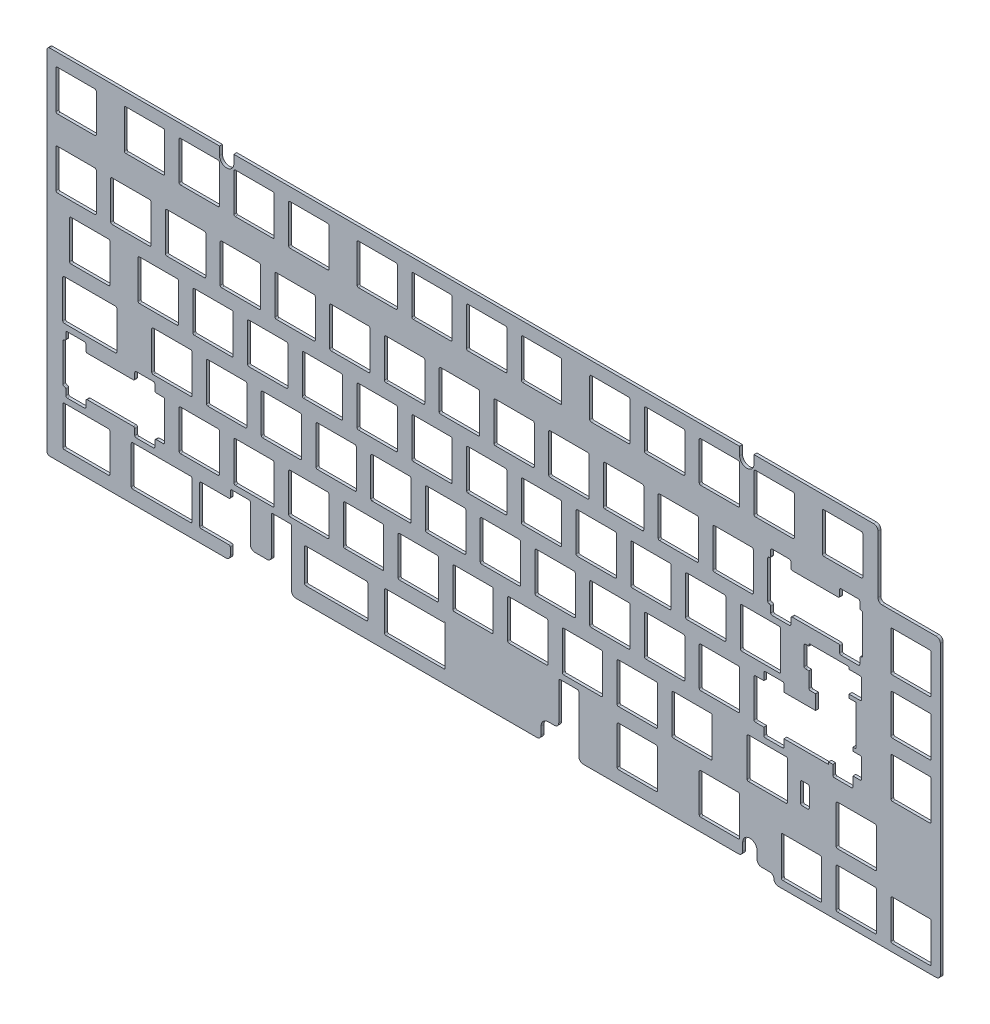
SolidWorks part; units mm, degrees
material "POM Acetal Copolymer"
ref_plane "Front Plane" through (0, 0, 0) normal (0, 0, 1) x (1, 0, 0)
ref_plane "Top Plane" through (0, 0, 0) normal (0, 1, 0) x (1, 0, 0)
ref_plane "Right Plane" through (0, 0, 0) normal (1, 0, 0) x (0, 0, -1)
sketch "Model" plane through (0, 0, 0) normal (0, 0, 1) x (1, 0, 0)
  line L0 (274.4928, 83.607) -> (287.4928, 83.607)
  line L1 (273.9928, 70.107) -> (273.9928, 75.3421)
  line L2 (8.8553, 129.8695) -> (8.8553, 63.082)
  line L3 (67.4518, 130.9695) -> (9.9553, 130.9695)
  line L4 (319.7678, 63.082) -> (319.7678, 106.4532)
  line L5 (195.4959, 7.957) -> (249.4928, 7.957)
  line L6 (86.9959, 28.958) -> (86.9959, 16.157)
  line L7 (187.4959, 29.458) -> (193.4959, 29.458)
  line L8 (193.9959, 28.958) -> (193.9959, 9.457)
  line L9 (186.9959, 16.157) -> (186.9959, 28.958)
  line L10 (87.4959, 29.458) -> (93.4959, 29.458)
  line L11 (126.357, 12.957) -> (126.357, 25.957)
  line L12 (62.0594, 12.957) -> (62.0594, 25.957)
  line L13 (38.2454, 12.957) -> (38.2454, 25.957)
  line L14 (14.4343, 12.957) -> (14.4343, 25.957)
  line L15 (72.207, 12.457) -> (62.5594, 12.457)
  line L16 (62.5594, 26.457) -> (72.207, 26.457)
  line L17 (59.3945, 25.957) -> (59.3945, 12.957)
  line L18 (58.8945, 12.457) -> (38.7454, 12.457)
  line L19 (38.7454, 26.457) -> (58.8945, 26.457)
  line L20 (30.8195, 25.957) -> (30.8195, 12.957)
  line L21 (30.3195, 12.457) -> (14.9343, 12.457)
  line L22 (14.9343, 26.457) -> (30.3195, 26.457)
  line L23 (93.9959, 28.958) -> (93.9959, 9.457)
  line L24 (146.9959, 12.457) -> (126.857, 12.457)
  line L25 (126.857, 26.457) -> (146.9959, 26.457)
  line L26 (147.4959, 26.7823) -> (147.4959, 12.957)
  line L27 (9.9553, 7.957) -> (71.207, 7.957)
  line L28 (95.4959, 7.957) -> (179.3625, 7.957)
  line L29 (263.3678, 5.0945) -> (318.2678, 5.0945)
  line L30 (180.8625, 12.157) -> (180.8625, 9.457)
  line L31 (250.9928, 12.157) -> (250.9928, 9.457)
  line L32 (255.9928, 12.157) -> (255.9928, 9.457)
  line L33 (183.3625, 14.657) -> (185.4959, 14.657)
  line L34 (81.207, 14.657) -> (85.4959, 14.657)
  line L35 (257.4928, 7.957) -> (260.371, 7.957)
  line L36 (8.8553, 63.082) -> (8.8553, 9.057)
  line L37 (319.7678, 63.082) -> (319.7678, 6.5945)
  line L38 (75.4518, 130.9695) -> (248.4268, 130.9695)
  line L39 (256.4268, 130.9695) -> (296.5553, 130.9695)
  line L40 (298.0553, 129.4695) -> (298.0553, 109.4532)
  line L41 (299.5553, 107.9532) -> (318.2678, 107.9532)
  line L42 (271.6572, 41.007) -> (273.6572, 41.007)
  line L43 (274.1572, 40.507) -> (274.1572, 36.507)
  line L44 (273.6572, 36.007) -> (271.6572, 36.007)
  line L45 (271.1572, 36.507) -> (271.1572, 40.507)
  line L46 (260.7295, 105.157) -> (260.7295, 103.157)
  line L47 (268.2295, 102.657) -> (284.2295, 102.657)
  line L48 (268.2295, 88.657) -> (284.2295, 88.657)
  line L49 (261.2295, 105.657) -> (267.2295, 105.657)
  line L50 (261.2295, 85.657) -> (267.2295, 85.657)
  line L51 (267.7295, 103.157) -> (267.7295, 105.157)
  line L52 (267.7295, 88.157) -> (267.7295, 86.157)
  line L53 (291.7295, 105.157) -> (291.7295, 103.157)
  line L54 (291.2295, 105.657) -> (285.2295, 105.657)
  line L55 (291.2295, 85.657) -> (285.2295, 85.657)
  line L56 (284.7295, 103.157) -> (284.7295, 105.157)
  line L57 (284.7295, 88.157) -> (284.7295, 86.157)
  line L58 (258.3508, 50.557) -> (258.3508, 48.057)
  line L59 (265.3508, 50.557) -> (280.8516, 50.557)
  line L60 (258.8508, 67.557) -> (264.8508, 67.557)
  line L61 (258.8508, 47.557) -> (264.8508, 47.557)
  line L62 (265.3508, 64.557) -> (265.3508, 67.057)
  line L63 (265.3508, 50.557) -> (265.3508, 48.057)
  line L64 (288.8508, 47.557) -> (282.8508, 47.557)
  line L65 (282.3508, 51.3421) -> (282.3508, 48.057)
  line L66 (15.4632, 48.0073) -> (15.4632, 46.007)
  line L67 (22.9632, 45.5073) -> (38.9632, 45.5073)
  line L68 (22.9632, 31.5073) -> (38.9632, 31.5073)
  line L69 (15.9632, 48.5073) -> (21.9632, 48.5073)
  line L70 (15.9632, 28.5073) -> (21.9632, 28.5073)
  line L71 (22.4632, 46.0073) -> (22.4632, 48.0073)
  line L72 (22.4632, 31.0073) -> (22.4632, 29.0073)
  line L73 (46.4632, 48.0073) -> (46.4632, 46.007)
  line L74 (45.9632, 48.5073) -> (39.9632, 48.5073)
  line L75 (45.9632, 28.5073) -> (39.9632, 28.5073)
  line L76 (39.4632, 46.0073) -> (39.4632, 48.0073)
  line L77 (39.4632, 31.0073) -> (39.4632, 29.0073)
  line L78 (258.3508, 50.557) -> (255.4453, 50.557)
  line L79 (276.3765, 69.607) -> (274.4928, 69.607)
  line L80 (276.3765, 64.557) -> (276.3765, 69.607)
  line L81 (292.3508, 82.2801) -> (292.3508, 75.8421)
  line L82 (292.3508, 58.2801) -> (292.3508, 51.8421)
  line L83 (291.8508, 82.7801) -> (287.9953, 82.7801)
  line L84 (255.4453, 64.557) -> (258.3508, 64.557)
  line L85 (290.3765, 74.0611) -> (290.3765, 60.0611)
  line L86 (254.9453, 64.057) -> (254.9453, 51.057)
  line L87 (287.9953, 75.3421) -> (291.8508, 75.3421)
  line L88 (289.3508, 58.7801) -> (291.8508, 58.7801)
  line L89 (290.3765, 74.0611) -> (287.9953, 74.0611)
  line L90 (287.9953, 74.0611) -> (287.9953, 75.3421)
  line L91 (289.3508, 58.7801) -> (289.3508, 60.0611)
  line L92 (289.3508, 60.0611) -> (290.3765, 60.0611)
  line L93 (282.3508, 51.3421) -> (280.8516, 51.3421)
  line L94 (280.8516, 51.3421) -> (280.8516, 50.557)
  line L95 (258.3508, 67.057) -> (258.3508, 64.557)
  line L96 (289.3508, 48.057) -> (289.3508, 51.3421)
  line L97 (291.8508, 51.3421) -> (289.3508, 51.3421)
  line L98 (287.9928, 83.107) -> (287.9953, 82.7801)
  line L99 (265.3508, 64.557) -> (276.3765, 64.557)
  line L100 (272.3508, 82.2801) -> (272.3508, 75.8421)
  line L101 (272.8508, 82.7801) -> (273.9928, 82.7801)
  line L102 (273.9928, 75.3421) -> (272.8508, 75.3421)
  line L103 (273.9928, 82.7801) -> (273.9928, 83.107)
  line L104 (259.7053, 89.157) -> (259.7053, 102.157)
  line L105 (292.7553, 102.157) -> (292.7553, 89.157)
  line L106 (291.7295, 86.157) -> (291.7295, 88.157)
  line L107 (292.2295, 88.657) -> (292.2553, 88.657)
  line L108 (292.2295, 102.657) -> (292.2553, 102.657)
  line L109 (260.2053, 102.657) -> (260.2295, 102.657)
  line L110 (260.7295, 86.157) -> (260.7295, 88.157)
  line L111 (260.2295, 88.657) -> (260.2053, 88.657)
  line L112 (49.8678, 45.007) -> (49.8678, 32.007)
  line L113 (46.4632, 29.0073) -> (46.4632, 31.007)
  line L114 (46.9632, 31.507) -> (49.3678, 31.507)
  line L115 (46.9632, 45.507) -> (49.3678, 45.507)
  line L116 (14.4365, 32.007) -> (14.4365, 45.007)
  line L117 (15.4632, 29.0073) -> (15.4632, 31.007)
  line L118 (14.9632, 31.507) -> (14.9365, 31.507)
  line L119 (14.9365, 45.507) -> (14.9632, 45.507)
  line L120 (79.707, 28.958) -> (79.707, 16.157)
  line L121 (72.707, 11.957) -> (72.707, 9.457)
  line L122 (72.707, 26.957) -> (72.707, 28.958)
  line L123 (73.207, 29.458) -> (79.207, 29.458)
  line L124 (120.5413, 13.957) -> (120.5413, 24.957)
  line L125 (99.0413, 13.457) -> (120.0413, 13.457)
  line L126 (98.5413, 24.957) -> (98.5413, 13.957)
  line L127 (120.0413, 25.457) -> (99.0413, 25.457)
  line L144 (12.5303, 112.4445) -> (25.5803, 112.4445)
  line L145 (26.0803, 112.9445) -> (26.0803, 125.9945)
  line L146 (25.5803, 126.4945) -> (12.5303, 126.4945)
  line L147 (12.0303, 125.9945) -> (12.0303, 112.9445)
  line L148 (36.3428, 112.4445) -> (49.3928, 112.4445)
  line L149 (49.8928, 112.9445) -> (49.8928, 125.9945)
  line L150 (49.3928, 126.4945) -> (36.3428, 126.4945)
  line L151 (35.8428, 125.9945) -> (35.8428, 112.9445)
  line L152 (93.4928, 112.4445) -> (106.5428, 112.4445)
  line L153 (107.0428, 112.9445) -> (107.0428, 125.9945)
  line L154 (106.5428, 126.4945) -> (93.4928, 126.4945)
  line L155 (92.9928, 125.9945) -> (92.9928, 112.9445)
  line L156 (117.3053, 112.4445) -> (130.3553, 112.4445)
  line L157 (130.8553, 112.9445) -> (130.8553, 125.9945)
  line L158 (130.3553, 126.4945) -> (117.3053, 126.4945)
  line L159 (116.8053, 125.9945) -> (116.8053, 112.9445)
  line L160 (136.3553, 112.4445) -> (149.4053, 112.4445)
  line L161 (149.9053, 112.9445) -> (149.9053, 125.9945)
  line L162 (149.4053, 126.4945) -> (136.3553, 126.4945)
  line L163 (135.8553, 125.9945) -> (135.8553, 112.9445)
  line L164 (155.4053, 112.4445) -> (168.4553, 112.4445)
  line L165 (168.9553, 112.9445) -> (168.9553, 125.9945)
  line L166 (168.4553, 126.4945) -> (155.4053, 126.4945)
  line L167 (154.9053, 125.9945) -> (154.9053, 112.9445)
  line L168 (174.4553, 112.4445) -> (187.5053, 112.4445)
  line L169 (188.0053, 112.9445) -> (188.0053, 125.9945)
  line L170 (187.5053, 126.4945) -> (174.4553, 126.4945)
  line L171 (173.9553, 125.9945) -> (173.9553, 112.9445)
  line L172 (198.2678, 112.4445) -> (211.3178, 112.4445)
  line L173 (211.8178, 112.9445) -> (211.8178, 125.9945)
  line L174 (211.3178, 126.4945) -> (198.2678, 126.4945)
  line L175 (197.7678, 125.9945) -> (197.7678, 112.9445)
  line L176 (217.3178, 112.4445) -> (230.3678, 112.4445)
  line L177 (230.8678, 112.9445) -> (230.8678, 125.9945)
  line L178 (230.3678, 126.4945) -> (217.3178, 126.4945)
  line L179 (216.8178, 125.9945) -> (216.8178, 112.9445)
  line L180 (279.2303, 112.4445) -> (292.2803, 112.4445)
  line L181 (292.7803, 112.9445) -> (292.7803, 125.9945)
  line L182 (292.2803, 126.4945) -> (279.2303, 126.4945)
  line L183 (278.7303, 125.9945) -> (278.7303, 112.9445)
  line L184 (303.0428, 88.632) -> (316.0928, 88.632)
  line L185 (316.5928, 89.132) -> (316.5928, 102.182)
  line L186 (316.0928, 102.682) -> (303.0428, 102.682)
  line L187 (302.5428, 102.182) -> (302.5428, 89.132)
  line L188 (283.9928, 26.7195) -> (297.0428, 26.7195)
  line L189 (297.5428, 27.2195) -> (297.5428, 40.2695)
  line L190 (297.0428, 40.7695) -> (283.9928, 40.7695)
  line L191 (283.4928, 40.2695) -> (283.4928, 27.2195)
  line L192 (303.0428, 7.6695) -> (316.0928, 7.6695)
  line L193 (316.5928, 8.1695) -> (316.5928, 21.2195)
  line L194 (316.0928, 21.7195) -> (303.0428, 21.7195)
  line L195 (302.5428, 21.2195) -> (302.5428, 8.1695)
  line L196 (283.9928, 7.6695) -> (297.0428, 7.6695)
  line L197 (297.5428, 8.1695) -> (297.5428, 21.2195)
  line L198 (297.0428, 21.7195) -> (283.9928, 21.7195)
  line L199 (283.4928, 21.2195) -> (283.4928, 8.1695)
  line L200 (264.9428, 7.6695) -> (277.9928, 7.6695)
  line L201 (278.4928, 8.1695) -> (278.4928, 21.2195)
  line L202 (277.9928, 21.7195) -> (264.9428, 21.7195)
  line L203 (264.4428, 21.2195) -> (264.4428, 8.1695)
  line L204 (236.3678, 12.432) -> (249.4178, 12.432)
  line L205 (249.9178, 12.932) -> (249.9178, 25.982)
  line L206 (249.4178, 26.482) -> (236.3678, 26.482)
  line L207 (235.8678, 25.982) -> (235.8678, 12.932)
  line L208 (207.7928, 12.432) -> (220.8428, 12.432)
  line L209 (221.3428, 12.932) -> (221.3428, 25.982)
  line L210 (220.8428, 26.482) -> (207.7928, 26.482)
  line L211 (207.2928, 25.982) -> (207.2928, 12.932)
  line L212 (253.0365, 31.482) -> (266.0865, 31.482)
  line L213 (266.5865, 31.982) -> (266.5865, 45.032)
  line L214 (266.0865, 45.532) -> (253.0365, 45.532)
  line L215 (252.5365, 45.032) -> (252.5365, 31.982)
  line L216 (226.8428, 31.482) -> (239.8928, 31.482)
  line L217 (240.3928, 31.982) -> (240.3928, 45.032)
  line L218 (239.8928, 45.532) -> (226.8428, 45.532)
  line L219 (226.3428, 45.032) -> (226.3428, 31.982)
  line L220 (207.7928, 31.482) -> (220.8428, 31.482)
  line L221 (221.3428, 31.982) -> (221.3428, 45.032)
  line L222 (220.8428, 45.532) -> (207.7928, 45.532)
  line L223 (207.2928, 45.032) -> (207.2928, 31.982)
  line L224 (188.7428, 31.482) -> (201.7928, 31.482)
  line L225 (202.2928, 31.982) -> (202.2928, 45.032)
  line L226 (201.7928, 45.532) -> (188.7428, 45.532)
  line L227 (188.2428, 45.032) -> (188.2428, 31.982)
  line L228 (169.6928, 31.482) -> (182.7428, 31.482)
  line L229 (183.2428, 31.982) -> (183.2428, 45.032)
  line L230 (182.7428, 45.532) -> (169.6928, 45.532)
  line L231 (169.1928, 45.032) -> (169.1928, 31.982)
  line L232 (150.6428, 31.482) -> (163.6928, 31.482)
  line L233 (164.1928, 31.982) -> (164.1928, 45.032)
  line L234 (163.6928, 45.532) -> (150.6428, 45.532)
  line L235 (150.1428, 45.032) -> (150.1428, 31.982)
  line L236 (131.5928, 31.482) -> (144.6428, 31.482)
  line L237 (145.1428, 31.982) -> (145.1428, 45.032)
  line L238 (144.6428, 45.532) -> (131.5928, 45.532)
  line L239 (131.0928, 45.032) -> (131.0928, 31.982)
  line L240 (112.5428, 31.482) -> (125.5928, 31.482)
  line L241 (126.0928, 31.982) -> (126.0928, 45.032)
  line L242 (125.5928, 45.532) -> (112.5428, 45.532)
  line L243 (112.0428, 45.032) -> (112.0428, 31.982)
  line L244 (93.4928, 31.482) -> (106.5428, 31.482)
  line L245 (107.0428, 31.982) -> (107.0428, 45.032)
  line L246 (106.5428, 45.532) -> (93.4928, 45.532)
  line L247 (92.9928, 45.032) -> (92.9928, 31.982)
  line L248 (74.4428, 31.482) -> (87.4928, 31.482)
  line L249 (87.9928, 31.982) -> (87.9928, 45.032)
  line L250 (87.4928, 45.532) -> (74.4428, 45.532)
  line L251 (73.9428, 45.032) -> (73.9428, 31.982)
  line L252 (55.3928, 31.482) -> (68.4428, 31.482)
  line L253 (68.9428, 31.982) -> (68.9428, 45.032)
  line L254 (68.4428, 45.532) -> (55.3928, 45.532)
  line L255 (54.8928, 45.032) -> (54.8928, 31.982)
  line L256 (45.8678, 50.532) -> (58.9178, 50.532)
  line L257 (59.4178, 51.032) -> (59.4178, 64.082)
  line L258 (58.9178, 64.582) -> (45.8678, 64.582)
  line L259 (45.3678, 64.082) -> (45.3678, 51.032)
  line L260 (64.9178, 50.532) -> (77.9678, 50.532)
  line L261 (78.4678, 51.032) -> (78.4678, 64.082)
  line L262 (77.9678, 64.582) -> (64.9178, 64.582)
  line L263 (64.4178, 64.082) -> (64.4178, 51.032)
  line L264 (83.9678, 50.532) -> (97.0178, 50.532)
  line L265 (97.5178, 51.032) -> (97.5178, 64.082)
  line L266 (97.0178, 64.582) -> (83.9678, 64.582)
  line L267 (83.4678, 64.082) -> (83.4678, 51.032)
  line L268 (103.0178, 50.532) -> (116.0678, 50.532)
  line L269 (116.5678, 51.032) -> (116.5678, 64.082)
  line L270 (116.0678, 64.582) -> (103.0178, 64.582)
  line L271 (102.5178, 64.082) -> (102.5178, 51.032)
  line L272 (122.0678, 50.532) -> (135.1178, 50.532)
  line L273 (135.6178, 51.032) -> (135.6178, 64.082)
  line L274 (135.1178, 64.582) -> (122.0678, 64.582)
  line L275 (121.5678, 64.082) -> (121.5678, 51.032)
  line L276 (141.1178, 50.532) -> (154.1678, 50.532)
  line L277 (154.6678, 51.032) -> (154.6678, 64.082)
  line L278 (154.1678, 64.582) -> (141.1178, 64.582)
  line L279 (140.6178, 64.082) -> (140.6178, 51.032)
  line L280 (160.1678, 50.532) -> (173.2178, 50.532)
  line L281 (173.7178, 51.032) -> (173.7178, 64.082)
  line L282 (173.2178, 64.582) -> (160.1678, 64.582)
  line L283 (159.6678, 64.082) -> (159.6678, 51.032)
  line L284 (179.2178, 50.532) -> (192.2678, 50.532)
  line L285 (192.7678, 51.032) -> (192.7678, 64.082)
  line L286 (192.2678, 64.582) -> (179.2178, 64.582)
  line L287 (178.7178, 64.082) -> (178.7178, 51.032)
  line L288 (198.2678, 50.532) -> (211.3178, 50.532)
  line L289 (211.8178, 51.032) -> (211.8178, 64.082)
  line L290 (211.3178, 64.582) -> (198.2678, 64.582)
  line L291 (197.7678, 64.082) -> (197.7678, 51.032)
  line L292 (217.3178, 50.532) -> (230.3678, 50.532)
  line L293 (230.8678, 51.032) -> (230.8678, 64.082)
  line L294 (230.3678, 64.582) -> (217.3178, 64.582)
  line L295 (216.8178, 64.082) -> (216.8178, 51.032)
  line L296 (236.3678, 50.532) -> (249.4178, 50.532)
  line L297 (249.9178, 51.032) -> (249.9178, 64.082)
  line L298 (249.4178, 64.582) -> (236.3678, 64.582)
  line L299 (235.8678, 64.082) -> (235.8678, 51.032)
  line L300 (17.2928, 69.582) -> (30.3428, 69.582)
  line L301 (30.8428, 70.082) -> (30.8428, 83.132)
  line L302 (30.3428, 83.632) -> (17.2928, 83.632)
  line L303 (16.7928, 83.132) -> (16.7928, 70.082)
  line L304 (12.5303, 88.632) -> (25.5803, 88.632)
  line L305 (26.0803, 89.132) -> (26.0803, 102.182)
  line L306 (25.5803, 102.682) -> (12.5303, 102.682)
  line L307 (12.0303, 102.182) -> (12.0303, 89.132)
  line L308 (31.5803, 88.632) -> (44.6303, 88.632)
  line L309 (45.1303, 89.132) -> (45.1303, 102.182)
  line L310 (44.6303, 102.682) -> (31.5803, 102.682)
  line L311 (31.0803, 102.182) -> (31.0803, 89.132)
  line L312 (50.6303, 88.632) -> (63.6803, 88.632)
  line L313 (64.1803, 89.132) -> (64.1803, 102.182)
  line L314 (63.6803, 102.682) -> (50.6303, 102.682)
  line L315 (50.1303, 102.182) -> (50.1303, 89.132)
  line L316 (69.6803, 88.632) -> (82.7303, 88.632)
  line L317 (83.2303, 89.132) -> (83.2303, 102.182)
  line L318 (82.7303, 102.682) -> (69.6803, 102.682)
  line L319 (69.1803, 102.182) -> (69.1803, 89.132)
  line L320 (88.7303, 88.632) -> (101.7803, 88.632)
  line L321 (102.2803, 89.132) -> (102.2803, 102.182)
  line L322 (101.7803, 102.682) -> (88.7303, 102.682)
  line L323 (88.2303, 102.182) -> (88.2303, 89.132)
  line L324 (107.7803, 88.632) -> (120.8303, 88.632)
  line L325 (121.3303, 89.132) -> (121.3303, 102.182)
  line L326 (120.8303, 102.682) -> (107.7803, 102.682)
  line L327 (107.2803, 102.182) -> (107.2803, 89.132)
  line L328 (126.8303, 88.632) -> (139.8803, 88.632)
  line L329 (140.3803, 89.132) -> (140.3803, 102.182)
  line L330 (139.8803, 102.682) -> (126.8303, 102.682)
  line L331 (126.3303, 102.182) -> (126.3303, 89.132)
  line L332 (145.8803, 88.632) -> (158.9303, 88.632)
  line L333 (159.4303, 89.132) -> (159.4303, 102.182)
  line L334 (158.9303, 102.682) -> (145.8803, 102.682)
  line L335 (145.3803, 102.182) -> (145.3803, 89.132)
  line L336 (164.9303, 88.632) -> (177.9803, 88.632)
  line L337 (178.4803, 89.132) -> (178.4803, 102.182)
  line L338 (177.9803, 102.682) -> (164.9303, 102.682)
  line L339 (164.4303, 102.182) -> (164.4303, 89.132)
  line L340 (183.9803, 88.632) -> (197.0303, 88.632)
  line L341 (197.5303, 89.132) -> (197.5303, 102.182)
  line L342 (197.0303, 102.682) -> (183.9803, 102.682)
  line L343 (183.4803, 102.182) -> (183.4803, 89.132)
  line L344 (203.0303, 88.632) -> (216.0803, 88.632)
  line L345 (216.5803, 89.132) -> (216.5803, 102.182)
  line L346 (216.0803, 102.682) -> (203.0303, 102.682)
  line L347 (202.5303, 102.182) -> (202.5303, 89.132)
  line L348 (222.0803, 88.632) -> (235.1303, 88.632)
  line L349 (235.6303, 89.132) -> (235.6303, 102.182)
  line L350 (235.1303, 102.682) -> (222.0803, 102.682)
  line L351 (221.5803, 102.182) -> (221.5803, 89.132)
  line L352 (241.1303, 88.632) -> (254.1803, 88.632)
  line L353 (254.6803, 89.132) -> (254.6803, 102.182)
  line L354 (254.1803, 102.682) -> (241.1303, 102.682)
  line L355 (240.6303, 102.182) -> (240.6303, 89.132)
  line L356 (41.1053, 69.582) -> (54.1553, 69.582)
  line L357 (54.6553, 70.082) -> (54.6553, 83.132)
  line L358 (54.1553, 83.632) -> (41.1053, 83.632)
  line L359 (40.6053, 83.132) -> (40.6053, 70.082)
  line L360 (60.1553, 69.582) -> (73.2053, 69.582)
  line L361 (73.7053, 70.082) -> (73.7053, 83.132)
  line L362 (73.2053, 83.632) -> (60.1553, 83.632)
  line L363 (59.6553, 83.132) -> (59.6553, 70.082)
  line L364 (79.2053, 69.582) -> (92.2553, 69.582)
  line L365 (92.7553, 70.082) -> (92.7553, 83.132)
  line L366 (92.2553, 83.632) -> (79.2053, 83.632)
  line L367 (78.7053, 83.132) -> (78.7053, 70.082)
  line L368 (98.2553, 69.582) -> (111.3053, 69.582)
  line L369 (111.8053, 70.082) -> (111.8053, 83.132)
  line L370 (111.3053, 83.632) -> (98.2553, 83.632)
  line L371 (97.7553, 83.132) -> (97.7553, 70.082)
  line L372 (117.3053, 69.582) -> (130.3553, 69.582)
  line L373 (130.8553, 70.082) -> (130.8553, 83.132)
  line L374 (130.3553, 83.632) -> (117.3053, 83.632)
  line L375 (116.8053, 83.132) -> (116.8053, 70.082)
  line L376 (136.3553, 69.582) -> (149.4053, 69.582)
  line L377 (149.9053, 70.082) -> (149.9053, 83.132)
  line L378 (149.4053, 83.632) -> (136.3553, 83.632)
  line L379 (135.8553, 83.132) -> (135.8553, 70.082)
  line L380 (155.4053, 69.582) -> (168.4553, 69.582)
  line L381 (168.9553, 70.082) -> (168.9553, 83.132)
  line L382 (168.4553, 83.632) -> (155.4053, 83.632)
  line L383 (154.9053, 83.132) -> (154.9053, 70.082)
  line L384 (174.4553, 69.582) -> (187.5053, 69.582)
  line L385 (188.0053, 70.082) -> (188.0053, 83.132)
  line L386 (187.5053, 83.632) -> (174.4553, 83.632)
  line L387 (173.9553, 83.132) -> (173.9553, 70.082)
  line L388 (193.5053, 69.582) -> (206.5553, 69.582)
  line L389 (207.0553, 70.082) -> (207.0553, 83.132)
  line L390 (206.5553, 83.632) -> (193.5053, 83.632)
  line L391 (193.0053, 83.132) -> (193.0053, 70.082)
  line L392 (212.5553, 69.582) -> (225.6053, 69.582)
  line L393 (226.1053, 70.082) -> (226.1053, 83.132)
  line L394 (225.6053, 83.632) -> (212.5553, 83.632)
  line L395 (212.0553, 83.132) -> (212.0553, 70.082)
  line L396 (231.6053, 69.582) -> (244.6553, 69.582)
  line L397 (245.1553, 70.082) -> (245.1553, 83.132)
  line L398 (244.6553, 83.632) -> (231.6053, 83.632)
  line L399 (231.1053, 83.132) -> (231.1053, 70.082)
  line L400 (250.6553, 69.582) -> (263.7053, 69.582)
  line L401 (264.2053, 70.082) -> (264.2053, 83.132)
  line L402 (263.7053, 83.632) -> (250.6553, 83.632)
  line L403 (250.1553, 83.132) -> (250.1553, 70.082)
  line L404 (303.0428, 69.582) -> (316.0928, 69.582)
  line L405 (316.5928, 70.082) -> (316.5928, 83.132)
  line L406 (316.0928, 83.632) -> (303.0428, 83.632)
  line L407 (302.5428, 83.132) -> (302.5428, 70.082)
  line L408 (303.0678, 64.582) -> (316.1178, 64.582)
  line L409 (302.5428, 51.057) -> (302.5428, 64.057)
  line L410 (316.0678, 50.532) -> (303.0678, 50.532)
  line L411 (316.5928, 64.107) -> (316.5928, 51.057)
  line L412 (32.699, 50.507) -> (14.9365, 50.507)
  line L413 (33.249, 64.057) -> (33.249, 51.057)
  line L414 (14.9365, 64.607) -> (32.699, 64.607)
  line L415 (14.3865, 51.057) -> (14.3865, 64.057)
  line L416 (236.3678, 112.4445) -> (249.4178, 112.4445)
  line L417 (249.9178, 112.9445) -> (249.9178, 125.9945)
  line L418 (249.4178, 126.4945) -> (236.3678, 126.4945)
  line L419 (235.8678, 125.9945) -> (235.8678, 112.9445)
  line L420 (255.4178, 112.4445) -> (268.4678, 112.4445)
  line L421 (268.9678, 112.9445) -> (268.9678, 125.9945)
  line L422 (268.4678, 126.4945) -> (255.4178, 126.4945)
  line L423 (254.9178, 125.9945) -> (254.9178, 112.9445)
  line L424 (55.3928, 112.4445) -> (68.4428, 112.4445)
  line L425 (68.9428, 112.9445) -> (68.9428, 125.9945)
  line L426 (68.4428, 126.4945) -> (55.3928, 126.4945)
  line L427 (54.8928, 125.9945) -> (54.8928, 112.9445)
  line L428 (74.4428, 112.4445) -> (87.4928, 112.4445)
  line L429 (87.9928, 112.9445) -> (87.9928, 125.9945)
  line L430 (87.4928, 126.4945) -> (74.4428, 126.4945)
  line L431 (73.9428, 125.9945) -> (73.9428, 112.9445)
  line L432 (67.4518, 130.9695) -> (75.4518, 130.9695)
  line L433 (248.4268, 130.9695) -> (256.4268, 130.9695)
  arc A0 (319.7678, 106.4532) -> (318.2678, 107.9532) centre (318.2678, 106.4532) ccw
  arc A1 (318.2678, 5.0945) -> (319.7678, 6.5945) centre (318.2678, 6.5945) ccw
  arc A2 (193.9959, 9.457) -> (195.4959, 7.957) centre (195.4959, 9.457) ccw
  arc A3 (273.9928, 70.107) -> (274.4928, 69.607) centre (274.4928, 70.107) ccw
  arc A4 (287.9928, 83.107) -> (287.4928, 83.607) centre (287.4928, 83.107) ccw
  arc A5 (274.4928, 83.607) -> (273.9928, 83.107) centre (274.4928, 83.107) ccw
  arc A6 (8.8553, 9.057) -> (9.9553, 7.957) centre (9.9553, 9.057) ccw
  arc A7 (9.9553, 130.9695) -> (8.8553, 129.8695) centre (9.9553, 129.8695) ccw
  arc A8 (85.4959, 14.657) -> (86.9959, 16.157) centre (85.4959, 16.157) ccw
  arc A9 (193.9959, 28.958) -> (193.4959, 29.458) centre (193.4959, 28.958) ccw
  arc A10 (187.4959, 29.458) -> (186.9959, 28.958) centre (187.4959, 28.958) ccw
  arc A11 (185.4959, 14.657) -> (186.9959, 16.157) centre (185.4959, 16.157) ccw
  arc A12 (87.4959, 29.458) -> (86.9959, 28.958) centre (87.4959, 28.958) ccw
  arc A13 (126.357, 12.957) -> (126.857, 12.457) centre (126.857, 12.957) ccw
  arc A14 (93.9959, 28.958) -> (93.4959, 29.458) centre (93.4959, 28.958) ccw
  arc A15 (38.7454, 26.457) -> (38.2454, 25.957) centre (38.7454, 25.957) ccw
  arc A16 (14.9343, 26.457) -> (14.4343, 25.957) centre (14.9343, 25.957) ccw
  arc A17 (62.0594, 12.957) -> (62.5594, 12.457) centre (62.5594, 12.957) ccw
  arc A18 (62.5594, 26.457) -> (62.0594, 25.957) centre (62.5594, 25.957) ccw
  arc A19 (38.2454, 12.957) -> (38.7454, 12.457) centre (38.7454, 12.957) ccw
  arc A20 (58.8945, 12.457) -> (59.3945, 12.957) centre (58.8945, 12.957) ccw
  arc A21 (59.3945, 25.957) -> (58.8945, 26.457) centre (58.8945, 25.957) ccw
  arc A22 (30.3195, 12.457) -> (30.8195, 12.957) centre (30.3195, 12.957) ccw
  arc A23 (14.4343, 12.957) -> (14.9343, 12.457) centre (14.9343, 12.957) ccw
  arc A24 (30.8195, 25.957) -> (30.3195, 26.457) centre (30.3195, 25.957) ccw
  arc A25 (126.857, 26.457) -> (126.357, 25.957) centre (126.857, 25.957) ccw
  arc A26 (146.9959, 12.457) -> (147.4959, 12.957) centre (146.9959, 12.957) ccw
  arc A27 (147.4959, 26.7823) -> (146.9959, 26.457) centre (147.4647, 26.2833) ccw
  arc A28 (93.9959, 9.457) -> (95.4959, 7.957) centre (95.4959, 9.457) ccw
  arc A29 (261.8694, 6.5258) -> (263.3678, 5.0945) centre (263.3678, 6.5945) ccw
  arc A30 (261.8694, 6.5258) -> (260.371, 7.957) centre (260.371, 6.457) ccw
  arc A31 (179.3625, 7.957) -> (180.8625, 9.457) centre (179.3625, 9.457) ccw
  arc A32 (255.9928, 9.457) -> (257.4928, 7.957) centre (257.4928, 9.457) ccw
  arc A33 (249.4928, 7.957) -> (250.9928, 9.457) centre (249.4928, 9.457) ccw
  arc A34 (255.9928, 12.157) -> (250.9928, 12.157) centre (253.4928, 12.157) ccw
  arc A35 (183.3625, 14.657) -> (180.8625, 12.157) centre (183.3625, 12.157) ccw
  arc A36 (298.0553, 129.4695) -> (296.5553, 130.9695) centre (296.5553, 129.4695) ccw
  arc A37 (298.0553, 109.4532) -> (299.5553, 107.9532) centre (299.5553, 109.4532) ccw
  arc A38 (271.6572, 41.007) -> (271.1572, 40.507) centre (271.6572, 40.507) ccw
  arc A39 (274.1572, 40.507) -> (273.6572, 41.007) centre (273.6572, 40.507) ccw
  arc A40 (273.6572, 36.007) -> (274.1572, 36.507) centre (273.6572, 36.507) ccw
  arc A41 (271.1572, 36.507) -> (271.6572, 36.007) centre (271.6572, 36.507) ccw
  arc A42 (260.2295, 102.657) -> (260.7295, 103.157) centre (260.2295, 103.157) ccw
  arc A43 (267.7295, 103.157) -> (268.2295, 102.657) centre (268.2295, 103.157) ccw
  arc A44 (261.2295, 105.657) -> (260.7295, 105.157) centre (261.2295, 105.157) ccw
  arc A45 (260.7295, 86.157) -> (261.2295, 85.657) centre (261.2295, 86.157) ccw
  arc A46 (267.7295, 105.157) -> (267.2295, 105.657) centre (267.2295, 105.157) ccw
  arc A47 (268.2295, 88.657) -> (267.7295, 88.157) centre (268.2295, 88.157) ccw
  arc A48 (267.2295, 85.657) -> (267.7295, 86.157) centre (267.2295, 86.157) ccw
  arc A49 (284.2295, 102.657) -> (284.7295, 103.157) centre (284.2295, 103.157) ccw
  arc A50 (291.7295, 105.157) -> (291.2295, 105.657) centre (291.2295, 105.157) ccw
  arc A51 (291.2295, 85.657) -> (291.7295, 86.157) centre (291.2295, 86.157) ccw
  arc A52 (285.2295, 105.657) -> (284.7295, 105.157) centre (285.2295, 105.157) ccw
  arc A53 (284.7295, 88.157) -> (284.2295, 88.657) centre (284.2295, 88.157) ccw
  arc A54 (284.7295, 86.157) -> (285.2295, 85.657) centre (285.2295, 86.157) ccw
  arc A55 (258.8508, 67.557) -> (258.3508, 67.057) centre (258.8508, 67.057) ccw
  arc A56 (258.3508, 48.057) -> (258.8508, 47.557) centre (258.8508, 48.057) ccw
  arc A57 (265.3508, 67.057) -> (264.8508, 67.557) centre (264.8508, 67.057) ccw
  arc A58 (264.8508, 47.557) -> (265.3508, 48.057) centre (264.8508, 48.057) ccw
  arc A59 (288.8508, 47.557) -> (289.3508, 48.057) centre (288.8508, 48.057) ccw
  arc A60 (282.3508, 48.057) -> (282.8508, 47.557) centre (282.8508, 48.057) ccw
  arc A61 (14.9632, 45.507) -> (15.4632, 46.007) centre (14.9632, 46.007) ccw
  arc A62 (22.4632, 46.0073) -> (22.9632, 45.5073) centre (22.9632, 46.0073) ccw
  arc A63 (15.9632, 48.5073) -> (15.4632, 48.0073) centre (15.9632, 48.0073) ccw
  arc A64 (15.4632, 29.0073) -> (15.9632, 28.5073) centre (15.9632, 29.0073) ccw
  arc A65 (22.4632, 48.0073) -> (21.9632, 48.5073) centre (21.9632, 48.0073) ccw
  arc A66 (22.9632, 31.5073) -> (22.4632, 31.0073) centre (22.9632, 31.0073) ccw
  arc A67 (21.9632, 28.5073) -> (22.4632, 29.0073) centre (21.9632, 29.0073) ccw
  arc A68 (38.9632, 45.5073) -> (39.4632, 46.0073) centre (38.9632, 46.0073) ccw
  arc A69 (46.4632, 48.0073) -> (45.9632, 48.5073) centre (45.9632, 48.0073) ccw
  arc A70 (45.9632, 28.5073) -> (46.4632, 29.0073) centre (45.9632, 29.0073) ccw
  arc A71 (39.9632, 48.5073) -> (39.4632, 48.0073) centre (39.9632, 48.0073) ccw
  arc A72 (39.4632, 31.0073) -> (38.9632, 31.5073) centre (38.9632, 31.0073) ccw
  arc A73 (39.4632, 29.0073) -> (39.9632, 28.5073) centre (39.9632, 29.0073) ccw
  arc A74 (291.8508, 51.3421) -> (292.3508, 51.8421) centre (291.8508, 51.8421) ccw
  arc A75 (292.3508, 82.2801) -> (291.8508, 82.7801) centre (291.8508, 82.2801) ccw
  arc A76 (292.3508, 58.2801) -> (291.8508, 58.7801) centre (291.8508, 58.2801) ccw
  arc A77 (291.8508, 75.3421) -> (292.3508, 75.8421) centre (291.8508, 75.8421) ccw
  arc A78 (272.8508, 82.7801) -> (272.3508, 82.2801) centre (272.8508, 82.2801) ccw
  arc A79 (272.3508, 75.8421) -> (272.8508, 75.3421) centre (272.8508, 75.8421) ccw
  arc A80 (259.7053, 89.157) -> (260.2053, 88.657) centre (260.2053, 89.157) ccw
  arc A81 (260.2053, 102.657) -> (259.7053, 102.157) centre (260.2053, 102.157) ccw
  arc A82 (292.2553, 88.657) -> (292.7553, 89.157) centre (292.2553, 89.157) ccw
  arc A83 (292.7553, 102.157) -> (292.2553, 102.657) centre (292.2553, 102.157) ccw
  arc A84 (292.2295, 88.657) -> (291.7295, 88.157) centre (292.2295, 88.157) ccw
  arc A85 (291.7295, 103.157) -> (292.2295, 102.657) centre (292.2295, 103.157) ccw
  arc A86 (260.7295, 88.157) -> (260.2295, 88.657) centre (260.2295, 88.157) ccw
  arc A87 (49.3678, 31.507) -> (49.8678, 32.007) centre (49.3678, 32.007) ccw
  arc A88 (49.8678, 45.007) -> (49.3678, 45.507) centre (49.3678, 45.007) ccw
  arc A89 (46.9632, 31.507) -> (46.4632, 31.007) centre (46.9632, 31.007) ccw
  arc A90 (46.4632, 46.007) -> (46.9632, 45.507) centre (46.9632, 46.007) ccw
  arc A91 (14.4365, 32.007) -> (14.9365, 31.507) centre (14.9365, 32.007) ccw
  arc A92 (14.9365, 45.507) -> (14.4365, 45.007) centre (14.9365, 45.007) ccw
  arc A93 (15.4632, 31.007) -> (14.9632, 31.507) centre (14.9632, 31.007) ccw
  arc A94 (72.707, 11.957) -> (72.207, 12.457) centre (72.207, 11.957) ccw
  arc A95 (72.207, 26.457) -> (72.707, 26.957) centre (72.207, 26.957) ccw
  arc A96 (73.207, 29.458) -> (72.707, 28.958) centre (73.207, 28.958) ccw
  arc A97 (79.707, 28.958) -> (79.207, 29.458) centre (79.207, 28.958) ccw
  arc A98 (71.207, 7.957) -> (72.707, 9.457) centre (71.207, 9.457) ccw
  arc A99 (79.707, 16.157) -> (81.207, 14.657) centre (81.207, 16.157) ccw
  arc A100 (255.4453, 64.557) -> (254.9453, 64.057) centre (255.4453, 64.057) ccw
  arc A101 (254.9453, 51.057) -> (255.4453, 50.557) centre (255.4453, 51.057) ccw
  arc A102 (120.0413, 13.457) -> (120.5413, 13.957) centre (120.0413, 13.957) ccw
  arc A103 (98.5413, 13.957) -> (99.0413, 13.457) centre (99.0413, 13.957) ccw
  arc A104 (99.0413, 25.457) -> (98.5413, 24.957) centre (99.0413, 24.957) ccw
  arc A105 (120.5413, 24.957) -> (120.0413, 25.457) centre (120.0413, 24.957) ccw
  arc A134 (303.0678, 64.582) -> (302.5428, 64.057) centre (303.0678, 64.057) ccw
  arc A135 (302.5428, 51.057) -> (303.0678, 50.532) centre (303.0678, 51.057) ccw
  arc A136 (316.0678, 50.532) -> (316.5928, 51.057) centre (316.0678, 51.057) ccw
  arc A137 (316.5928, 64.107) -> (316.1178, 64.582) centre (316.1178, 64.107) ccw
  arc A138 (14.3865, 51.057) -> (14.9365, 50.507) centre (14.9365, 51.057) ccw
  arc A139 (32.699, 50.507) -> (33.249, 51.057) centre (32.699, 51.057) ccw
  arc A140 (33.249, 64.057) -> (32.699, 64.607) centre (32.699, 64.057) ccw
  arc A141 (14.9365, 64.607) -> (14.3865, 64.057) centre (14.9365, 64.057) ccw
  arc A142 (25.5803, 112.4445) -> (26.0803, 112.9445) centre (25.5803, 112.9445) ccw
  arc A143 (26.0803, 125.9945) -> (25.5803, 126.4945) centre (25.5803, 125.9945) ccw
  arc A144 (12.5303, 126.4945) -> (12.0303, 125.9945) centre (12.5303, 125.9945) ccw
  arc A145 (12.0303, 112.9445) -> (12.5303, 112.4445) centre (12.5303, 112.9445) ccw
  arc A146 (49.3928, 112.4445) -> (49.8928, 112.9445) centre (49.3928, 112.9445) ccw
  arc A147 (49.8928, 125.9945) -> (49.3928, 126.4945) centre (49.3928, 125.9945) ccw
  arc A148 (36.3428, 126.4945) -> (35.8428, 125.9945) centre (36.3428, 125.9945) ccw
  arc A149 (35.8428, 112.9445) -> (36.3428, 112.4445) centre (36.3428, 112.9445) ccw
  arc A150 (106.5428, 112.4445) -> (107.0428, 112.9445) centre (106.5428, 112.9445) ccw
  arc A151 (107.0428, 125.9945) -> (106.5428, 126.4945) centre (106.5428, 125.9945) ccw
  arc A152 (93.4928, 126.4945) -> (92.9928, 125.9945) centre (93.4928, 125.9945) ccw
  arc A153 (92.9928, 112.9445) -> (93.4928, 112.4445) centre (93.4928, 112.9445) ccw
  arc A154 (130.3553, 112.4445) -> (130.8553, 112.9445) centre (130.3553, 112.9445) ccw
  arc A155 (130.8553, 125.9945) -> (130.3553, 126.4945) centre (130.3553, 125.9945) ccw
  arc A156 (117.3053, 126.4945) -> (116.8053, 125.9945) centre (117.3053, 125.9945) ccw
  arc A157 (116.8053, 112.9445) -> (117.3053, 112.4445) centre (117.3053, 112.9445) ccw
  arc A158 (149.4053, 112.4445) -> (149.9053, 112.9445) centre (149.4053, 112.9445) ccw
  arc A159 (149.9053, 125.9945) -> (149.4053, 126.4945) centre (149.4053, 125.9945) ccw
  arc A160 (136.3553, 126.4945) -> (135.8553, 125.9945) centre (136.3553, 125.9945) ccw
  arc A161 (135.8553, 112.9445) -> (136.3553, 112.4445) centre (136.3553, 112.9445) ccw
  arc A162 (168.4553, 112.4445) -> (168.9553, 112.9445) centre (168.4553, 112.9445) ccw
  arc A163 (168.9553, 125.9945) -> (168.4553, 126.4945) centre (168.4553, 125.9945) ccw
  arc A164 (155.4053, 126.4945) -> (154.9053, 125.9945) centre (155.4053, 125.9945) ccw
  arc A165 (154.9053, 112.9445) -> (155.4053, 112.4445) centre (155.4053, 112.9445) ccw
  arc A166 (187.5053, 112.4445) -> (188.0053, 112.9445) centre (187.5053, 112.9445) ccw
  arc A167 (188.0053, 125.9945) -> (187.5053, 126.4945) centre (187.5053, 125.9945) ccw
  arc A168 (174.4553, 126.4945) -> (173.9553, 125.9945) centre (174.4553, 125.9945) ccw
  arc A169 (173.9553, 112.9445) -> (174.4553, 112.4445) centre (174.4553, 112.9445) ccw
  arc A170 (211.3178, 112.4445) -> (211.8178, 112.9445) centre (211.3178, 112.9445) ccw
  arc A171 (211.8178, 125.9945) -> (211.3178, 126.4945) centre (211.3178, 125.9945) ccw
  arc A172 (198.2678, 126.4945) -> (197.7678, 125.9945) centre (198.2678, 125.9945) ccw
  arc A173 (197.7678, 112.9445) -> (198.2678, 112.4445) centre (198.2678, 112.9445) ccw
  arc A174 (230.3678, 112.4445) -> (230.8678, 112.9445) centre (230.3678, 112.9445) ccw
  arc A175 (230.8678, 125.9945) -> (230.3678, 126.4945) centre (230.3678, 125.9945) ccw
  arc A176 (217.3178, 126.4945) -> (216.8178, 125.9945) centre (217.3178, 125.9945) ccw
  arc A177 (216.8178, 112.9445) -> (217.3178, 112.4445) centre (217.3178, 112.9445) ccw
  arc A178 (292.2803, 112.4445) -> (292.7803, 112.9445) centre (292.2803, 112.9445) ccw
  arc A179 (292.7803, 125.9945) -> (292.2803, 126.4945) centre (292.2803, 125.9945) ccw
  arc A180 (279.2303, 126.4945) -> (278.7303, 125.9945) centre (279.2303, 125.9945) ccw
  arc A181 (278.7303, 112.9445) -> (279.2303, 112.4445) centre (279.2303, 112.9445) ccw
  arc A182 (316.0928, 88.632) -> (316.5928, 89.132) centre (316.0928, 89.132) ccw
  arc A183 (316.5928, 102.182) -> (316.0928, 102.682) centre (316.0928, 102.182) ccw
  arc A184 (303.0428, 102.682) -> (302.5428, 102.182) centre (303.0428, 102.182) ccw
  arc A185 (302.5428, 89.132) -> (303.0428, 88.632) centre (303.0428, 89.132) ccw
  arc A186 (297.0428, 26.7195) -> (297.5428, 27.2195) centre (297.0428, 27.2195) ccw
  arc A187 (297.5428, 40.2695) -> (297.0428, 40.7695) centre (297.0428, 40.2695) ccw
  arc A188 (283.9928, 40.7695) -> (283.4928, 40.2695) centre (283.9928, 40.2695) ccw
  arc A189 (283.4928, 27.2195) -> (283.9928, 26.7195) centre (283.9928, 27.2195) ccw
  arc A190 (316.0928, 7.6695) -> (316.5928, 8.1695) centre (316.0928, 8.1695) ccw
  arc A191 (316.5928, 21.2195) -> (316.0928, 21.7195) centre (316.0928, 21.2195) ccw
  arc A192 (303.0428, 21.7195) -> (302.5428, 21.2195) centre (303.0428, 21.2195) ccw
  arc A193 (302.5428, 8.1695) -> (303.0428, 7.6695) centre (303.0428, 8.1695) ccw
  arc A194 (297.0428, 7.6695) -> (297.5428, 8.1695) centre (297.0428, 8.1695) ccw
  arc A195 (297.5428, 21.2195) -> (297.0428, 21.7195) centre (297.0428, 21.2195) ccw
  arc A196 (283.9928, 21.7195) -> (283.4928, 21.2195) centre (283.9928, 21.2195) ccw
  arc A197 (283.4928, 8.1695) -> (283.9928, 7.6695) centre (283.9928, 8.1695) ccw
  arc A198 (277.9928, 7.6695) -> (278.4928, 8.1695) centre (277.9928, 8.1695) ccw
  arc A199 (278.4928, 21.2195) -> (277.9928, 21.7195) centre (277.9928, 21.2195) ccw
  arc A200 (264.9428, 21.7195) -> (264.4428, 21.2195) centre (264.9428, 21.2195) ccw
  arc A201 (264.4428, 8.1695) -> (264.9428, 7.6695) centre (264.9428, 8.1695) ccw
  arc A202 (249.4178, 12.432) -> (249.9178, 12.932) centre (249.4178, 12.932) ccw
  arc A203 (249.9178, 25.982) -> (249.4178, 26.482) centre (249.4178, 25.982) ccw
  arc A204 (236.3678, 26.482) -> (235.8678, 25.982) centre (236.3678, 25.982) ccw
  arc A205 (235.8678, 12.932) -> (236.3678, 12.432) centre (236.3678, 12.932) ccw
  arc A206 (220.8428, 12.432) -> (221.3428, 12.932) centre (220.8428, 12.932) ccw
  arc A207 (221.3428, 25.982) -> (220.8428, 26.482) centre (220.8428, 25.982) ccw
  arc A208 (207.7928, 26.482) -> (207.2928, 25.982) centre (207.7928, 25.982) ccw
  arc A209 (207.2928, 12.932) -> (207.7928, 12.432) centre (207.7928, 12.932) ccw
  arc A210 (266.0865, 31.482) -> (266.5865, 31.982) centre (266.0865, 31.982) ccw
  arc A211 (266.5865, 45.032) -> (266.0865, 45.532) centre (266.0865, 45.032) ccw
  arc A212 (253.0365, 45.532) -> (252.5365, 45.032) centre (253.0365, 45.032) ccw
  arc A213 (252.5365, 31.982) -> (253.0365, 31.482) centre (253.0365, 31.982) ccw
  arc A214 (239.8928, 31.482) -> (240.3928, 31.982) centre (239.8928, 31.982) ccw
  arc A215 (240.3928, 45.032) -> (239.8928, 45.532) centre (239.8928, 45.032) ccw
  arc A216 (226.8428, 45.532) -> (226.3428, 45.032) centre (226.8428, 45.032) ccw
  arc A217 (226.3428, 31.982) -> (226.8428, 31.482) centre (226.8428, 31.982) ccw
  arc A218 (220.8428, 31.482) -> (221.3428, 31.982) centre (220.8428, 31.982) ccw
  arc A219 (221.3428, 45.032) -> (220.8428, 45.532) centre (220.8428, 45.032) ccw
  arc A220 (207.7928, 45.532) -> (207.2928, 45.032) centre (207.7928, 45.032) ccw
  arc A221 (207.2928, 31.982) -> (207.7928, 31.482) centre (207.7928, 31.982) ccw
  arc A222 (201.7928, 31.482) -> (202.2928, 31.982) centre (201.7928, 31.982) ccw
  arc A223 (202.2928, 45.032) -> (201.7928, 45.532) centre (201.7928, 45.032) ccw
  arc A224 (188.7428, 45.532) -> (188.2428, 45.032) centre (188.7428, 45.032) ccw
  arc A225 (188.2428, 31.982) -> (188.7428, 31.482) centre (188.7428, 31.982) ccw
  arc A226 (182.7428, 31.482) -> (183.2428, 31.982) centre (182.7428, 31.982) ccw
  arc A227 (183.2428, 45.032) -> (182.7428, 45.532) centre (182.7428, 45.032) ccw
  arc A228 (169.6928, 45.532) -> (169.1928, 45.032) centre (169.6928, 45.032) ccw
  arc A229 (169.1928, 31.982) -> (169.6928, 31.482) centre (169.6928, 31.982) ccw
  arc A230 (163.6928, 31.482) -> (164.1928, 31.982) centre (163.6928, 31.982) ccw
  arc A231 (164.1928, 45.032) -> (163.6928, 45.532) centre (163.6928, 45.032) ccw
  arc A232 (150.6428, 45.532) -> (150.1428, 45.032) centre (150.6428, 45.032) ccw
  arc A233 (150.1428, 31.982) -> (150.6428, 31.482) centre (150.6428, 31.982) ccw
  arc A234 (144.6428, 31.482) -> (145.1428, 31.982) centre (144.6428, 31.982) ccw
  arc A235 (145.1428, 45.032) -> (144.6428, 45.532) centre (144.6428, 45.032) ccw
  arc A236 (131.5928, 45.532) -> (131.0928, 45.032) centre (131.5928, 45.032) ccw
  arc A237 (131.0928, 31.982) -> (131.5928, 31.482) centre (131.5928, 31.982) ccw
  arc A238 (125.5928, 31.482) -> (126.0928, 31.982) centre (125.5928, 31.982) ccw
  arc A239 (126.0928, 45.032) -> (125.5928, 45.532) centre (125.5928, 45.032) ccw
  arc A240 (112.5428, 45.532) -> (112.0428, 45.032) centre (112.5428, 45.032) ccw
  arc A241 (112.0428, 31.982) -> (112.5428, 31.482) centre (112.5428, 31.982) ccw
  arc A242 (106.5428, 31.482) -> (107.0428, 31.982) centre (106.5428, 31.982) ccw
  arc A243 (107.0428, 45.032) -> (106.5428, 45.532) centre (106.5428, 45.032) ccw
  arc A244 (93.4928, 45.532) -> (92.9928, 45.032) centre (93.4928, 45.032) ccw
  arc A245 (92.9928, 31.982) -> (93.4928, 31.482) centre (93.4928, 31.982) ccw
  arc A246 (87.4928, 31.482) -> (87.9928, 31.982) centre (87.4928, 31.982) ccw
  arc A247 (87.9928, 45.032) -> (87.4928, 45.532) centre (87.4928, 45.032) ccw
  arc A248 (74.4428, 45.532) -> (73.9428, 45.032) centre (74.4428, 45.032) ccw
  arc A249 (73.9428, 31.982) -> (74.4428, 31.482) centre (74.4428, 31.982) ccw
  arc A250 (68.4428, 31.482) -> (68.9428, 31.982) centre (68.4428, 31.982) ccw
  arc A251 (68.9428, 45.032) -> (68.4428, 45.532) centre (68.4428, 45.032) ccw
  arc A252 (55.3928, 45.532) -> (54.8928, 45.032) centre (55.3928, 45.032) ccw
  arc A253 (54.8928, 31.982) -> (55.3928, 31.482) centre (55.3928, 31.982) ccw
  arc A254 (58.9178, 50.532) -> (59.4178, 51.032) centre (58.9178, 51.032) ccw
  arc A255 (59.4178, 64.082) -> (58.9178, 64.582) centre (58.9178, 64.082) ccw
  arc A256 (45.8678, 64.582) -> (45.3678, 64.082) centre (45.8678, 64.082) ccw
  arc A257 (45.3678, 51.032) -> (45.8678, 50.532) centre (45.8678, 51.032) ccw
  arc A258 (77.9678, 50.532) -> (78.4678, 51.032) centre (77.9678, 51.032) ccw
  arc A259 (78.4678, 64.082) -> (77.9678, 64.582) centre (77.9678, 64.082) ccw
  arc A260 (64.9178, 64.582) -> (64.4178, 64.082) centre (64.9178, 64.082) ccw
  arc A261 (64.4178, 51.032) -> (64.9178, 50.532) centre (64.9178, 51.032) ccw
  arc A262 (97.0178, 50.532) -> (97.5178, 51.032) centre (97.0178, 51.032) ccw
  arc A263 (97.5178, 64.082) -> (97.0178, 64.582) centre (97.0178, 64.082) ccw
  arc A264 (83.9678, 64.582) -> (83.4678, 64.082) centre (83.9678, 64.082) ccw
  arc A265 (83.4678, 51.032) -> (83.9678, 50.532) centre (83.9678, 51.032) ccw
  arc A266 (116.0678, 50.532) -> (116.5678, 51.032) centre (116.0678, 51.032) ccw
  arc A267 (116.5678, 64.082) -> (116.0678, 64.582) centre (116.0678, 64.082) ccw
  arc A268 (103.0178, 64.582) -> (102.5178, 64.082) centre (103.0178, 64.082) ccw
  arc A269 (102.5178, 51.032) -> (103.0178, 50.532) centre (103.0178, 51.032) ccw
  arc A270 (135.1178, 50.532) -> (135.6178, 51.032) centre (135.1178, 51.032) ccw
  arc A271 (135.6178, 64.082) -> (135.1178, 64.582) centre (135.1178, 64.082) ccw
  arc A272 (122.0678, 64.582) -> (121.5678, 64.082) centre (122.0678, 64.082) ccw
  arc A273 (121.5678, 51.032) -> (122.0678, 50.532) centre (122.0678, 51.032) ccw
  arc A274 (154.1678, 50.532) -> (154.6678, 51.032) centre (154.1678, 51.032) ccw
  arc A275 (154.6678, 64.082) -> (154.1678, 64.582) centre (154.1678, 64.082) ccw
  arc A276 (141.1178, 64.582) -> (140.6178, 64.082) centre (141.1178, 64.082) ccw
  arc A277 (140.6178, 51.032) -> (141.1178, 50.532) centre (141.1178, 51.032) ccw
  arc A278 (173.2178, 50.532) -> (173.7178, 51.032) centre (173.2178, 51.032) ccw
  arc A279 (173.7178, 64.082) -> (173.2178, 64.582) centre (173.2178, 64.082) ccw
  arc A280 (160.1678, 64.582) -> (159.6678, 64.082) centre (160.1678, 64.082) ccw
  arc A281 (159.6678, 51.032) -> (160.1678, 50.532) centre (160.1678, 51.032) ccw
  arc A282 (192.2678, 50.532) -> (192.7678, 51.032) centre (192.2678, 51.032) ccw
  arc A283 (192.7678, 64.082) -> (192.2678, 64.582) centre (192.2678, 64.082) ccw
  arc A284 (179.2178, 64.582) -> (178.7178, 64.082) centre (179.2178, 64.082) ccw
  arc A285 (178.7178, 51.032) -> (179.2178, 50.532) centre (179.2178, 51.032) ccw
  arc A286 (211.3178, 50.532) -> (211.8178, 51.032) centre (211.3178, 51.032) ccw
  arc A287 (211.8178, 64.082) -> (211.3178, 64.582) centre (211.3178, 64.082) ccw
  arc A288 (198.2678, 64.582) -> (197.7678, 64.082) centre (198.2678, 64.082) ccw
  arc A289 (197.7678, 51.032) -> (198.2678, 50.532) centre (198.2678, 51.032) ccw
  arc A290 (230.3678, 50.532) -> (230.8678, 51.032) centre (230.3678, 51.032) ccw
  arc A291 (230.8678, 64.082) -> (230.3678, 64.582) centre (230.3678, 64.082) ccw
  arc A292 (217.3178, 64.582) -> (216.8178, 64.082) centre (217.3178, 64.082) ccw
  arc A293 (216.8178, 51.032) -> (217.3178, 50.532) centre (217.3178, 51.032) ccw
  arc A294 (249.4178, 50.532) -> (249.9178, 51.032) centre (249.4178, 51.032) ccw
  arc A295 (249.9178, 64.082) -> (249.4178, 64.582) centre (249.4178, 64.082) ccw
  arc A296 (236.3678, 64.582) -> (235.8678, 64.082) centre (236.3678, 64.082) ccw
  arc A297 (235.8678, 51.032) -> (236.3678, 50.532) centre (236.3678, 51.032) ccw
  arc A298 (30.3428, 69.582) -> (30.8428, 70.082) centre (30.3428, 70.082) ccw
  arc A299 (30.8428, 83.132) -> (30.3428, 83.632) centre (30.3428, 83.132) ccw
  arc A300 (17.2928, 83.632) -> (16.7928, 83.132) centre (17.2928, 83.132) ccw
  arc A301 (16.7928, 70.082) -> (17.2928, 69.582) centre (17.2928, 70.082) ccw
  arc A302 (25.5803, 88.632) -> (26.0803, 89.132) centre (25.5803, 89.132) ccw
  arc A303 (26.0803, 102.182) -> (25.5803, 102.682) centre (25.5803, 102.182) ccw
  arc A304 (12.5303, 102.682) -> (12.0303, 102.182) centre (12.5303, 102.182) ccw
  arc A305 (12.0303, 89.132) -> (12.5303, 88.632) centre (12.5303, 89.132) ccw
  arc A306 (44.6303, 88.632) -> (45.1303, 89.132) centre (44.6303, 89.132) ccw
  arc A307 (45.1303, 102.182) -> (44.6303, 102.682) centre (44.6303, 102.182) ccw
  arc A308 (31.5803, 102.682) -> (31.0803, 102.182) centre (31.5803, 102.182) ccw
  arc A309 (31.0803, 89.132) -> (31.5803, 88.632) centre (31.5803, 89.132) ccw
  arc A310 (63.6803, 88.632) -> (64.1803, 89.132) centre (63.6803, 89.132) ccw
  arc A311 (64.1803, 102.182) -> (63.6803, 102.682) centre (63.6803, 102.182) ccw
  arc A312 (50.6303, 102.682) -> (50.1303, 102.182) centre (50.6303, 102.182) ccw
  arc A313 (50.1303, 89.132) -> (50.6303, 88.632) centre (50.6303, 89.132) ccw
  arc A314 (82.7303, 88.632) -> (83.2303, 89.132) centre (82.7303, 89.132) ccw
  arc A315 (83.2303, 102.182) -> (82.7303, 102.682) centre (82.7303, 102.182) ccw
  arc A316 (69.6803, 102.682) -> (69.1803, 102.182) centre (69.6803, 102.182) ccw
  arc A317 (69.1803, 89.132) -> (69.6803, 88.632) centre (69.6803, 89.132) ccw
  arc A318 (101.7803, 88.632) -> (102.2803, 89.132) centre (101.7803, 89.132) ccw
  arc A319 (102.2803, 102.182) -> (101.7803, 102.682) centre (101.7803, 102.182) ccw
  arc A320 (88.7303, 102.682) -> (88.2303, 102.182) centre (88.7303, 102.182) ccw
  arc A321 (88.2303, 89.132) -> (88.7303, 88.632) centre (88.7303, 89.132) ccw
  arc A322 (120.8303, 88.632) -> (121.3303, 89.132) centre (120.8303, 89.132) ccw
  arc A323 (121.3303, 102.182) -> (120.8303, 102.682) centre (120.8303, 102.182) ccw
  arc A324 (107.7803, 102.682) -> (107.2803, 102.182) centre (107.7803, 102.182) ccw
  arc A325 (107.2803, 89.132) -> (107.7803, 88.632) centre (107.7803, 89.132) ccw
  arc A326 (139.8803, 88.632) -> (140.3803, 89.132) centre (139.8803, 89.132) ccw
  arc A327 (140.3803, 102.182) -> (139.8803, 102.682) centre (139.8803, 102.182) ccw
  arc A328 (126.8303, 102.682) -> (126.3303, 102.182) centre (126.8303, 102.182) ccw
  arc A329 (126.3303, 89.132) -> (126.8303, 88.632) centre (126.8303, 89.132) ccw
  arc A330 (158.9303, 88.632) -> (159.4303, 89.132) centre (158.9303, 89.132) ccw
  arc A331 (159.4303, 102.182) -> (158.9303, 102.682) centre (158.9303, 102.182) ccw
  arc A332 (145.8803, 102.682) -> (145.3803, 102.182) centre (145.8803, 102.182) ccw
  arc A333 (145.3803, 89.132) -> (145.8803, 88.632) centre (145.8803, 89.132) ccw
  arc A334 (177.9803, 88.632) -> (178.4803, 89.132) centre (177.9803, 89.132) ccw
  arc A335 (178.4803, 102.182) -> (177.9803, 102.682) centre (177.9803, 102.182) ccw
  arc A336 (164.9303, 102.682) -> (164.4303, 102.182) centre (164.9303, 102.182) ccw
  arc A337 (164.4303, 89.132) -> (164.9303, 88.632) centre (164.9303, 89.132) ccw
  arc A338 (197.0303, 88.632) -> (197.5303, 89.132) centre (197.0303, 89.132) ccw
  arc A339 (197.5303, 102.182) -> (197.0303, 102.682) centre (197.0303, 102.182) ccw
  arc A340 (183.9803, 102.682) -> (183.4803, 102.182) centre (183.9803, 102.182) ccw
  arc A341 (183.4803, 89.132) -> (183.9803, 88.632) centre (183.9803, 89.132) ccw
  arc A342 (216.0803, 88.632) -> (216.5803, 89.132) centre (216.0803, 89.132) ccw
  arc A343 (216.5803, 102.182) -> (216.0803, 102.682) centre (216.0803, 102.182) ccw
  arc A344 (203.0303, 102.682) -> (202.5303, 102.182) centre (203.0303, 102.182) ccw
  arc A345 (202.5303, 89.132) -> (203.0303, 88.632) centre (203.0303, 89.132) ccw
  arc A346 (235.1303, 88.632) -> (235.6303, 89.132) centre (235.1303, 89.132) ccw
  arc A347 (235.6303, 102.182) -> (235.1303, 102.682) centre (235.1303, 102.182) ccw
  arc A348 (222.0803, 102.682) -> (221.5803, 102.182) centre (222.0803, 102.182) ccw
  arc A349 (221.5803, 89.132) -> (222.0803, 88.632) centre (222.0803, 89.132) ccw
  arc A350 (254.1803, 88.632) -> (254.6803, 89.132) centre (254.1803, 89.132) ccw
  arc A351 (254.6803, 102.182) -> (254.1803, 102.682) centre (254.1803, 102.182) ccw
  arc A352 (241.1303, 102.682) -> (240.6303, 102.182) centre (241.1303, 102.182) ccw
  arc A353 (240.6303, 89.132) -> (241.1303, 88.632) centre (241.1303, 89.132) ccw
  arc A354 (54.1553, 69.582) -> (54.6553, 70.082) centre (54.1553, 70.082) ccw
  arc A355 (54.6553, 83.132) -> (54.1553, 83.632) centre (54.1553, 83.132) ccw
  arc A356 (41.1053, 83.632) -> (40.6053, 83.132) centre (41.1053, 83.132) ccw
  arc A357 (40.6053, 70.082) -> (41.1053, 69.582) centre (41.1053, 70.082) ccw
  arc A358 (73.2053, 69.582) -> (73.7053, 70.082) centre (73.2053, 70.082) ccw
  arc A359 (73.7053, 83.132) -> (73.2053, 83.632) centre (73.2053, 83.132) ccw
  arc A360 (60.1553, 83.632) -> (59.6553, 83.132) centre (60.1553, 83.132) ccw
  arc A361 (59.6553, 70.082) -> (60.1553, 69.582) centre (60.1553, 70.082) ccw
  arc A362 (92.2553, 69.582) -> (92.7553, 70.082) centre (92.2553, 70.082) ccw
  arc A363 (92.7553, 83.132) -> (92.2553, 83.632) centre (92.2553, 83.132) ccw
  arc A364 (79.2053, 83.632) -> (78.7053, 83.132) centre (79.2053, 83.132) ccw
  arc A365 (78.7053, 70.082) -> (79.2053, 69.582) centre (79.2053, 70.082) ccw
  arc A366 (111.3053, 69.582) -> (111.8053, 70.082) centre (111.3053, 70.082) ccw
  arc A367 (111.8053, 83.132) -> (111.3053, 83.632) centre (111.3053, 83.132) ccw
  arc A368 (98.2553, 83.632) -> (97.7553, 83.132) centre (98.2553, 83.132) ccw
  arc A369 (97.7553, 70.082) -> (98.2553, 69.582) centre (98.2553, 70.082) ccw
  arc A370 (130.3553, 69.582) -> (130.8553, 70.082) centre (130.3553, 70.082) ccw
  arc A371 (130.8553, 83.132) -> (130.3553, 83.632) centre (130.3553, 83.132) ccw
  arc A372 (117.3053, 83.632) -> (116.8053, 83.132) centre (117.3053, 83.132) ccw
  arc A373 (116.8053, 70.082) -> (117.3053, 69.582) centre (117.3053, 70.082) ccw
  arc A374 (149.4053, 69.582) -> (149.9053, 70.082) centre (149.4053, 70.082) ccw
  arc A375 (149.9053, 83.132) -> (149.4053, 83.632) centre (149.4053, 83.132) ccw
  arc A376 (136.3553, 83.632) -> (135.8553, 83.132) centre (136.3553, 83.132) ccw
  arc A377 (135.8553, 70.082) -> (136.3553, 69.582) centre (136.3553, 70.082) ccw
  arc A378 (168.4553, 69.582) -> (168.9553, 70.082) centre (168.4553, 70.082) ccw
  arc A379 (168.9553, 83.132) -> (168.4553, 83.632) centre (168.4553, 83.132) ccw
  arc A380 (155.4053, 83.632) -> (154.9053, 83.132) centre (155.4053, 83.132) ccw
  arc A381 (154.9053, 70.082) -> (155.4053, 69.582) centre (155.4053, 70.082) ccw
  arc A382 (187.5053, 69.582) -> (188.0053, 70.082) centre (187.5053, 70.082) ccw
  arc A383 (188.0053, 83.132) -> (187.5053, 83.632) centre (187.5053, 83.132) ccw
  arc A384 (174.4553, 83.632) -> (173.9553, 83.132) centre (174.4553, 83.132) ccw
  arc A385 (173.9553, 70.082) -> (174.4553, 69.582) centre (174.4553, 70.082) ccw
  arc A386 (206.5553, 69.582) -> (207.0553, 70.082) centre (206.5553, 70.082) ccw
  arc A387 (207.0553, 83.132) -> (206.5553, 83.632) centre (206.5553, 83.132) ccw
  arc A388 (193.5053, 83.632) -> (193.0053, 83.132) centre (193.5053, 83.132) ccw
  arc A389 (193.0053, 70.082) -> (193.5053, 69.582) centre (193.5053, 70.082) ccw
  arc A390 (225.6053, 69.582) -> (226.1053, 70.082) centre (225.6053, 70.082) ccw
  arc A391 (226.1053, 83.132) -> (225.6053, 83.632) centre (225.6053, 83.132) ccw
  arc A392 (212.5553, 83.632) -> (212.0553, 83.132) centre (212.5553, 83.132) ccw
  arc A393 (212.0553, 70.082) -> (212.5553, 69.582) centre (212.5553, 70.082) ccw
  arc A394 (244.6553, 69.582) -> (245.1553, 70.082) centre (244.6553, 70.082) ccw
  arc A395 (245.1553, 83.132) -> (244.6553, 83.632) centre (244.6553, 83.132) ccw
  arc A396 (231.6053, 83.632) -> (231.1053, 83.132) centre (231.6053, 83.132) ccw
  arc A397 (231.1053, 70.082) -> (231.6053, 69.582) centre (231.6053, 70.082) ccw
  arc A398 (263.7053, 69.582) -> (264.2053, 70.082) centre (263.7053, 70.082) ccw
  arc A399 (264.2053, 83.132) -> (263.7053, 83.632) centre (263.7053, 83.132) ccw
  arc A400 (250.6553, 83.632) -> (250.1553, 83.132) centre (250.6553, 83.132) ccw
  arc A401 (250.1553, 70.082) -> (250.6553, 69.582) centre (250.6553, 70.082) ccw
  arc A402 (316.0928, 69.582) -> (316.5928, 70.082) centre (316.0928, 70.082) ccw
  arc A403 (316.5928, 83.132) -> (316.0928, 83.632) centre (316.0928, 83.132) ccw
  arc A404 (303.0428, 83.632) -> (302.5428, 83.132) centre (303.0428, 83.132) ccw
  arc A405 (302.5428, 70.082) -> (303.0428, 69.582) centre (303.0428, 70.082) ccw
  arc A406 (249.4178, 112.4445) -> (249.9178, 112.9445) centre (249.4178, 112.9445) ccw
  arc A407 (249.9178, 125.9945) -> (249.4178, 126.4945) centre (249.4178, 125.9945) ccw
  arc A408 (236.3678, 126.4945) -> (235.8678, 125.9945) centre (236.3678, 125.9945) ccw
  arc A409 (235.8678, 112.9445) -> (236.3678, 112.4445) centre (236.3678, 112.9445) ccw
  arc A410 (268.4678, 112.4445) -> (268.9678, 112.9445) centre (268.4678, 112.9445) ccw
  arc A411 (268.9678, 125.9945) -> (268.4678, 126.4945) centre (268.4678, 125.9945) ccw
  arc A412 (255.4178, 126.4945) -> (254.9178, 125.9945) centre (255.4178, 125.9945) ccw
  arc A413 (254.9178, 112.9445) -> (255.4178, 112.4445) centre (255.4178, 112.9445) ccw
  arc A414 (68.4428, 112.4445) -> (68.9428, 112.9445) centre (68.4428, 112.9445) ccw
  arc A415 (68.9428, 125.9945) -> (68.4428, 126.4945) centre (68.4428, 125.9945) ccw
  arc A416 (55.3928, 126.4945) -> (54.8928, 125.9945) centre (55.3928, 125.9945) ccw
  arc A417 (54.8928, 112.9445) -> (55.3928, 112.4445) centre (55.3928, 112.9445) ccw
  arc A418 (87.4928, 112.4445) -> (87.9928, 112.9445) centre (87.4928, 112.9445) ccw
  arc A419 (87.9928, 125.9945) -> (87.4928, 126.4945) centre (87.4928, 125.9945) ccw
  arc A420 (74.4428, 126.4945) -> (73.9428, 125.9945) centre (74.4428, 125.9945) ccw
  arc A421 (73.9428, 112.9445) -> (74.4428, 112.4445) centre (74.4428, 112.9445) ccw
extrude "Boss-Extrude1" add sketch "Model" along normal blind 1 contours L120 A99 L34 A8 L6 A12 L10 A14 L23 A28 L28 A31 L30 A35 L33 A11 L9 A10 L7 A9 L8 A2 L5 A33 L31 A34 L32 A32 L35 A30 A29 L29 A1 L37 L4 A0 L41 A37 L40 A36 L39 L433 L38 L432 L3 A7 L2 L36 A6 L27 A98 region at (165.9365, 69.1281, 0)
ref_plane "Plane1" through (164.3115, 0, 0) normal (-1, 0, 0) x (0, 0, 1)
sketch "Sketch3" plane through (0, 0, 1) normal (0, 0, 1) x (1, 0, 0)
  line L0 (274.1572, 40.507) -> (274.1572, 36.507) construction
  line L1 (271.1572, 40.507) -> (274.1572, 40.507)
  line L2 (271.1572, 40.507) -> (271.1572, 34.007)
  line L3 (271.6572, 33.507) -> (273.6572, 33.507)
  line L4 (274.1572, 40.507) -> (274.1572, 34.007)
  arc A0 (274.1572, 34.007) -> (273.6572, 33.507) centre (273.6572, 34.007) cw
  arc A1 (271.6572, 33.507) -> (271.1572, 34.007) centre (271.6572, 34.007) cw
  dimension "D2" = 0.5
  dimension "D1" = 7
extrude "Cut-Extrude2" cut sketch "Sketch3" against normal blind 1.3
sketch "Sketch1" plane through (0, 0, 1) normal (0, 0, 1) x (1, 0, 0)
  line L0 (68.9518, 130.7195) -> (68.9518, 130.9695)
  line L1 (73.9518, 130.7195) -> (73.9518, 130.9695)
  line L2 (254.9268, 130.7195) -> (254.9268, 130.9695)
  line L3 (254.9268, 130.7195) -> (249.9268, 130.7195)
  line L4 (249.9268, 130.7195) -> (249.9268, 128.1033)
  line L5 (254.9268, 128.1033) -> (254.9268, 130.7195)
  line L6 (254.9268, 130.7195) -> (249.9268, 130.7195)
  line L7 (249.9268, 130.7195) -> (249.9268, 128.1033)
  line L8 (254.9268, 128.1033) -> (254.9268, 130.7195)
  line L9 (73.9518, 130.7195) -> (68.9518, 130.7195)
  line L10 (68.9518, 130.7195) -> (68.9518, 128.1033)
  line L11 (73.9518, 128.1033) -> (73.9518, 130.7195)
  line L12 (73.9518, 130.7195) -> (68.9518, 130.7195)
  line L13 (68.9518, 130.7195) -> (68.9518, 128.1033)
  line L14 (73.9518, 128.1033) -> (73.9518, 130.7195)
  line L15 (249.9268, 130.7195) -> (249.9268, 130.9695)
  line L40 (296.5553, 130.9695) -> (9.9553, 130.9695)
  line L41 (8.8553, 129.8695) -> (8.8553, 9.057)
  line L42 (9.9553, 7.957) -> (71.207, 7.957)
  line L43 (72.707, 9.457) -> (72.707, 11.957)
  line L44 (72.207, 12.457) -> (62.5594, 12.457)
  line L45 (62.0594, 12.957) -> (62.0594, 25.957)
  line L46 (62.5594, 26.457) -> (72.207, 26.457)
  line L47 (72.707, 26.957) -> (72.707, 28.958)
  line L48 (73.207, 29.458) -> (79.207, 29.458)
  line L49 (79.707, 28.958) -> (79.707, 16.157)
  line L50 (81.207, 14.657) -> (85.4959, 14.657)
  line L51 (86.9959, 16.157) -> (86.9959, 28.958)
  line L52 (87.4959, 29.458) -> (93.4959, 29.458)
  line L53 (93.9959, 28.958) -> (93.9959, 9.457)
  line L54 (95.4959, 7.957) -> (179.3625, 7.957)
  line L55 (180.8625, 9.457) -> (180.8625, 12.157)
  line L56 (183.3625, 14.657) -> (185.4959, 14.657)
  line L57 (186.9959, 16.157) -> (186.9959, 28.958)
  line L58 (187.4959, 29.458) -> (193.4959, 29.458)
  line L59 (193.9959, 28.958) -> (193.9959, 9.457)
  line L60 (195.4959, 7.957) -> (249.4928, 7.957)
  line L61 (250.9928, 9.457) -> (250.9928, 12.157)
  line L62 (255.9928, 12.157) -> (255.9928, 9.457)
  line L63 (257.4928, 7.957) -> (260.371, 7.957)
  line L64 (263.3678, 5.0945) -> (318.2678, 5.0945)
  line L65 (319.7678, 6.5945) -> (319.7678, 106.4532)
  line L66 (318.2678, 107.9532) -> (299.5553, 107.9532)
  line L67 (298.0553, 109.4532) -> (298.0553, 129.4695)
  line L68 (296.5553, 130.9695) -> (9.9553, 130.9695)
  line L69 (8.8553, 129.8695) -> (8.8553, 9.057)
  line L70 (9.9553, 7.957) -> (71.207, 7.957)
  line L71 (72.707, 9.457) -> (72.707, 11.957)
  line L72 (72.207, 12.457) -> (62.5594, 12.457)
  line L73 (62.0594, 12.957) -> (62.0594, 25.957)
  line L74 (62.5594, 26.457) -> (72.207, 26.457)
  line L75 (72.707, 26.957) -> (72.707, 28.958)
  line L76 (73.207, 29.458) -> (79.207, 29.458)
  line L77 (79.707, 28.958) -> (79.707, 16.157)
  line L78 (81.207, 14.657) -> (85.4959, 14.657)
  line L79 (86.9959, 16.157) -> (86.9959, 28.958)
  line L80 (87.4959, 29.458) -> (93.4959, 29.458)
  line L81 (93.9959, 28.958) -> (93.9959, 9.457)
  line L82 (95.4959, 7.957) -> (179.3625, 7.957)
  line L83 (180.8625, 9.457) -> (180.8625, 12.157)
  line L84 (183.3625, 14.657) -> (185.4959, 14.657)
  line L85 (186.9959, 16.157) -> (186.9959, 28.958)
  line L86 (187.4959, 29.458) -> (193.4959, 29.458)
  line L87 (193.9959, 28.958) -> (193.9959, 9.457)
  line L88 (195.4959, 7.957) -> (249.4928, 7.957)
  line L89 (250.9928, 9.457) -> (250.9928, 12.157)
  line L90 (255.9928, 12.157) -> (255.9928, 9.457)
  line L91 (257.4928, 7.957) -> (260.371, 7.957)
  line L92 (263.3678, 5.0945) -> (318.2678, 5.0945)
  line L93 (319.7678, 6.5945) -> (319.7678, 106.4532)
  line L94 (318.2678, 107.9532) -> (299.5553, 107.9532)
  line L95 (298.0553, 109.4532) -> (298.0553, 129.4695)
  arc A1 (249.9268, 128.1033) -> (254.9268, 128.1033) centre (252.4268, 128.1033) ccw
  arc A2 (249.9268, 128.1033) -> (254.9268, 128.1033) centre (252.4268, 128.1033) ccw
  arc A3 (68.9518, 128.1033) -> (73.9518, 128.1033) centre (71.4518, 128.1033) ccw
  arc A4 (68.9518, 128.1033) -> (73.9518, 128.1033) centre (71.4518, 128.1033) ccw
  arc A33 (298.0553, 129.4695) -> (296.5553, 130.9695) centre (296.5553, 129.4695) ccw
  arc A34 (9.9553, 130.9695) -> (8.8553, 129.8695) centre (9.9553, 129.8695) ccw
  arc A35 (8.8553, 9.057) -> (9.9553, 7.957) centre (9.9553, 9.057) ccw
  arc A36 (71.207, 7.957) -> (72.707, 9.457) centre (71.207, 9.457) ccw
  arc A37 (72.707, 11.957) -> (72.207, 12.457) centre (72.207, 11.957) ccw
  arc A38 (62.0594, 12.957) -> (62.5594, 12.457) centre (62.5594, 12.957) ccw
  arc A39 (62.5594, 26.457) -> (62.0594, 25.957) centre (62.5594, 25.957) ccw
  arc A40 (72.207, 26.457) -> (72.707, 26.957) centre (72.207, 26.957) ccw
  arc A41 (73.207, 29.458) -> (72.707, 28.958) centre (73.207, 28.958) ccw
  arc A42 (79.707, 28.958) -> (79.207, 29.458) centre (79.207, 28.958) ccw
  arc A43 (79.707, 16.157) -> (81.207, 14.657) centre (81.207, 16.157) ccw
  arc A44 (85.4959, 14.657) -> (86.9959, 16.157) centre (85.4959, 16.157) ccw
  arc A45 (87.4959, 29.458) -> (86.9959, 28.958) centre (87.4959, 28.958) ccw
  arc A47 (93.9959, 9.457) -> (95.4959, 7.957) centre (95.4959, 9.457) ccw
  arc A48 (179.3625, 7.957) -> (180.8625, 9.457) centre (179.3625, 9.457) ccw
  arc A49 (183.3625, 14.657) -> (180.8625, 12.157) centre (183.3625, 12.157) ccw
  arc A50 (185.4959, 14.657) -> (186.9959, 16.157) centre (185.4959, 16.157) ccw
  arc A51 (187.4959, 29.458) -> (186.9959, 28.958) centre (187.4959, 28.958) ccw
  arc A52 (193.9959, 28.958) -> (193.4959, 29.458) centre (193.4959, 28.958) ccw
  arc A53 (193.9959, 9.457) -> (195.4959, 7.957) centre (195.4959, 9.457) ccw
  arc A54 (249.4928, 7.957) -> (250.9928, 9.457) centre (249.4928, 9.457) ccw
  arc A55 (255.9928, 12.157) -> (250.9928, 12.157) centre (253.4928, 12.157) ccw
  arc A56 (255.9928, 9.457) -> (257.4928, 7.957) centre (257.4928, 9.457) ccw
  arc A57 (261.8694, 6.5258) -> (260.371, 7.957) centre (260.371, 6.457) ccw
  arc A58 (261.8694, 6.5258) -> (263.3678, 5.0945) centre (263.3678, 6.5945) ccw
  arc A59 (318.2678, 5.0945) -> (319.7678, 6.5945) centre (318.2678, 6.5945) ccw
  arc A60 (319.7678, 106.4532) -> (318.2678, 107.9532) centre (318.2678, 106.4532) ccw
  arc A61 (9.9553, 130.9695) -> (8.8553, 129.8695) centre (9.9553, 129.8695) ccw
  arc A62 (298.0553, 129.4695) -> (296.5553, 130.9695) centre (296.5553, 129.4695) ccw
  arc A64 (8.8553, 9.057) -> (9.9553, 7.957) centre (9.9553, 9.057) ccw
  arc A65 (71.207, 7.957) -> (72.707, 9.457) centre (71.207, 9.457) ccw
  arc A66 (72.707, 11.957) -> (72.207, 12.457) centre (72.207, 11.957) ccw
  arc A67 (62.0594, 12.957) -> (62.5594, 12.457) centre (62.5594, 12.957) ccw
  arc A68 (62.5594, 26.457) -> (62.0594, 25.957) centre (62.5594, 25.957) ccw
  arc A69 (72.207, 26.457) -> (72.707, 26.957) centre (72.207, 26.957) ccw
  arc A70 (73.207, 29.458) -> (72.707, 28.958) centre (73.207, 28.958) ccw
  arc A71 (79.707, 28.958) -> (79.207, 29.458) centre (79.207, 28.958) ccw
  arc A72 (79.707, 16.157) -> (81.207, 14.657) centre (81.207, 16.157) ccw
  arc A73 (85.4959, 14.657) -> (86.9959, 16.157) centre (85.4959, 16.157) ccw
  arc A74 (87.4959, 29.458) -> (86.9959, 28.958) centre (87.4959, 28.958) ccw
  arc A76 (93.9959, 9.457) -> (95.4959, 7.957) centre (95.4959, 9.457) ccw
  arc A77 (179.3625, 7.957) -> (180.8625, 9.457) centre (179.3625, 9.457) ccw
  arc A78 (183.3625, 14.657) -> (180.8625, 12.157) centre (183.3625, 12.157) ccw
  arc A79 (185.4959, 14.657) -> (186.9959, 16.157) centre (185.4959, 16.157) ccw
  arc A80 (187.4959, 29.458) -> (186.9959, 28.958) centre (187.4959, 28.958) ccw
  arc A81 (193.9959, 28.958) -> (193.4959, 29.458) centre (193.4959, 28.958) ccw
  arc A82 (193.9959, 9.457) -> (195.4959, 7.957) centre (195.4959, 9.457) ccw
  arc A83 (249.4928, 7.957) -> (250.9928, 9.457) centre (249.4928, 9.457) ccw
  arc A84 (255.9928, 12.157) -> (250.9928, 12.157) centre (253.4928, 12.157) ccw
  arc A85 (255.9928, 9.457) -> (257.4928, 7.957) centre (257.4928, 9.457) ccw
  arc A86 (261.8694, 6.5258) -> (260.371, 7.957) centre (260.371, 6.457) ccw
  arc A87 (261.8694, 6.5258) -> (263.3678, 5.0945) centre (263.3678, 6.5945) ccw
  arc A88 (318.2678, 5.0945) -> (319.7678, 6.5945) centre (318.2678, 6.5945) ccw
  arc A89 (319.7678, 106.4532) -> (318.2678, 107.9532) centre (318.2678, 106.4532) ccw
  arc A95 (93.9959, 28.958) -> (93.4959, 29.458) centre (93.4959, 28.958) ccw
  arc A96 (93.9959, 28.958) -> (93.4959, 29.458) centre (93.4959, 28.958) ccw
  arc A97 (298.0553, 109.4532) -> (299.5553, 107.9532) centre (299.5553, 109.4532) ccw
  arc A98 (298.0553, 109.4532) -> (299.5553, 107.9532) centre (299.5553, 109.4532) ccw
  dimension "D1" = 0
  dimension "D2" = 0
  dimension "D3" = 0
extrude "Cut-Extrude1" cut sketch "Sketch1" against normal blind 10 contours L13 A4 L14 L12 | L1 L68 L0 L12 | L7 A2 L8 L6 | L2 L68 L15 L6 region at (71.4518, 130.8445, 1) region at (71.4518, 128.3956, 1) region at (252.4268, 130.8445, 1) region at (252.4268, 128.3956, 1)
sketch "Sketch2" plane through (0, 0, 1) normal (0, 0, 1) x (1, 0, 0)
  line L0 (319.7678, 106.5732) -> (321.8078, 106.5732)
  line L1 (322.8078, 105.5732) -> (322.8078, 103.0119)
  line L2 (319.7678, 101.5982) -> (322.8078, 101.5982) construction
  line L3 (322.8078, 102.6332) -> (319.7678, 102.6332) construction
  line L4 (322.8078, 97.6232) -> (322.8078, 100.1845)
  line L5 (319.7678, 96.6232) -> (321.8078, 96.6232)
  line L6 (321.2378, 106.5732) -> (321.2378, 42.5232) construction
  line L7 (110.8338, 3.5504) -> (112.7953, 7.957)
  line L8 (88.0453, 7.957) -> (90.0068, 3.5504)
  line L9 (101.9533, 2.9571) -> (109.9202, 2.9571)
  line L10 (90.9204, 2.9571) -> (98.8873, 2.9571)
  line L11 (319.7678, 32.5732) -> (321.8078, 32.5732)
  line L12 (322.8078, 33.5732) -> (322.8078, 36.1345)
  line L13 (319.7678, 42.5232) -> (321.8078, 42.5232)
  line L14 (322.8078, 41.5232) -> (322.8078, 38.9619)
  line L15 (319.7678, 106.4532) -> (319.7678, 6.5945) construction
  line L16 (296.5553, 129.9695) -> (255.9268, 129.9695)
  line L17 (255.9268, 129.9695) -> (255.9268, 128.1033)
  line L18 (248.9268, 128.1033) -> (248.9268, 129.9695)
  line L19 (248.9268, 129.9695) -> (74.9518, 129.9695)
  line L20 (74.9518, 129.9695) -> (74.9518, 128.1033)
  line L21 (67.9518, 128.1033) -> (67.9518, 129.9695)
  line L22 (67.9518, 129.9695) -> (9.9553, 129.9695)
  line L23 (9.8553, 129.8695) -> (9.8553, 9.057)
  line L24 (9.9553, 8.957) -> (71.207, 8.957)
  line L25 (71.707, 9.457) -> (71.707, 11.457)
  line L26 (71.707, 11.457) -> (62.5594, 11.457)
  line L27 (61.0594, 12.957) -> (61.0594, 25.957)
  line L28 (62.5594, 27.457) -> (71.707, 27.457)
  line L29 (71.707, 27.457) -> (71.707, 28.958)
  line L30 (73.207, 30.458) -> (79.207, 30.458)
  line L31 (80.707, 28.958) -> (80.707, 16.157)
  line L32 (81.207, 15.657) -> (85.4959, 15.657)
  line L33 (85.9959, 16.157) -> (85.9959, 28.958)
  line L34 (296.5553, 130.9695) -> (254.9268, 130.9695)
  line L35 (254.9268, 130.9695) -> (254.9268, 128.1033)
  line L37 (254.9268, 130.9695) -> (254.9268, 128.1033)
  line L39 (249.9268, 128.1033) -> (249.9268, 130.9695)
  line L41 (8.8553, 129.8695) -> (8.8553, 9.057)
  line L42 (9.9553, 7.957) -> (71.207, 7.957)
  line L43 (72.707, 9.457) -> (72.707, 11.957)
  line L44 (72.207, 12.457) -> (62.5594, 12.457)
  line L45 (62.0594, 12.957) -> (62.0594, 25.957)
  line L46 (62.5594, 26.457) -> (72.207, 26.457)
  line L47 (72.707, 26.957) -> (72.707, 28.958)
  line L48 (73.207, 29.458) -> (79.207, 29.458)
  line L49 (79.707, 28.958) -> (79.707, 16.157)
  line L50 (81.207, 14.657) -> (85.4959, 14.657)
  line L51 (86.9959, 16.157) -> (86.9959, 28.958)
  line L52 (87.4959, 29.458) -> (93.4959, 29.458)
  line L53 (93.9959, 28.958) -> (93.9959, 9.457)
  line L54 (95.4959, 7.957) -> (179.3625, 7.957)
  line L55 (180.8625, 9.457) -> (180.8625, 12.157)
  line L56 (183.3625, 14.657) -> (185.4959, 14.657)
  line L57 (186.9959, 16.157) -> (186.9959, 28.958)
  line L58 (187.4959, 29.458) -> (193.4959, 29.458)
  line L59 (193.9959, 28.958) -> (193.9959, 9.457)
  line L60 (195.4959, 7.957) -> (249.4928, 7.957)
  line L61 (250.9928, 9.457) -> (250.9928, 12.157)
  line L62 (255.9928, 12.157) -> (255.9928, 9.457)
  line L63 (257.4928, 7.957) -> (260.371, 7.957)
  line L64 (263.3678, 5.0945) -> (318.2678, 5.0945)
  line L65 (319.7678, 6.5945) -> (319.7678, 106.4532)
  line L66 (318.2678, 107.9532) -> (299.5553, 107.9532)
  line L67 (298.0553, 109.4532) -> (298.0553, 129.4695)
  line L68 (296.5553, 130.9695) -> (254.9268, 130.9695)
  line L75 (8.8553, 129.8695) -> (8.8553, 9.057)
  line L76 (9.9553, 7.957) -> (71.207, 7.957)
  line L77 (72.707, 9.457) -> (72.707, 11.957)
  line L78 (72.207, 12.457) -> (62.5594, 12.457)
  line L79 (62.0594, 12.957) -> (62.0594, 25.957)
  line L80 (62.5594, 26.457) -> (72.207, 26.457)
  line L81 (72.707, 26.957) -> (72.707, 28.958)
  line L82 (73.207, 29.458) -> (79.207, 29.458)
  line L83 (79.707, 28.958) -> (79.707, 16.157)
  line L84 (81.207, 14.657) -> (85.4959, 14.657)
  line L85 (86.9959, 16.157) -> (86.9959, 28.958)
  line L86 (87.4959, 29.458) -> (93.4959, 29.458)
  line L87 (93.9959, 28.958) -> (93.9959, 9.457)
  line L88 (95.4959, 7.957) -> (179.3625, 7.957)
  line L89 (180.8625, 9.457) -> (180.8625, 12.157)
  line L90 (183.3625, 14.657) -> (185.4959, 14.657)
  line L91 (186.9959, 16.157) -> (186.9959, 28.958)
  line L92 (187.4959, 29.458) -> (193.4959, 29.458)
  line L93 (193.9959, 28.958) -> (193.9959, 9.457)
  line L94 (195.4959, 7.957) -> (249.4928, 7.957)
  line L95 (250.9928, 9.457) -> (250.9928, 12.157)
  line L96 (255.9928, 12.157) -> (255.9928, 9.457)
  line L97 (257.4928, 7.957) -> (260.371, 7.957)
  line L98 (263.3678, 5.0945) -> (318.2678, 5.0945)
  line L99 (319.7678, 6.5945) -> (319.7678, 106.4532)
  line L100 (318.2678, 107.9532) -> (299.5553, 107.9532)
  line L101 (298.0553, 109.4532) -> (298.0553, 129.4695)
  line L102 (87.4959, 30.458) -> (93.4959, 30.458)
  line L103 (94.9959, 28.958) -> (94.9959, 9.457)
  line L104 (95.4959, 8.957) -> (179.3625, 8.957)
  line L105 (179.8625, 9.457) -> (179.8625, 12.157)
  line L107 (183.3625, 15.657) -> (185.4959, 15.657)
  line L108 (185.9959, 16.157) -> (185.9959, 28.958)
  line L109 (187.4959, 30.458) -> (193.4959, 30.458)
  line L110 (194.9959, 28.958) -> (194.9959, 9.457)
  line L111 (195.4959, 8.957) -> (249.4928, 8.957)
  line L112 (249.9928, 9.457) -> (249.9928, 12.157)
  line L113 (256.9928, 12.157) -> (256.9928, 9.457)
  line L114 (257.4928, 8.957) -> (260.371, 8.957)
  line L115 (263.3678, 6.0945) -> (318.2678, 6.0945)
  line L116 (318.7678, 6.5945) -> (318.7678, 106.4532)
  line L117 (318.2678, 106.9532) -> (299.5553, 106.9532)
  line L118 (297.0553, 109.4532) -> (297.0553, 129.4695)
  line L119 (273.3053, 130.9695) -> (275.2667, 135.3762)
  line L120 (276.1803, 135.9695) -> (284.1473, 135.9695)
  line L121 (287.2133, 135.9695) -> (295.1803, 135.9695)
  line L122 (296.0939, 135.3762) -> (298.0553, 130.9695)
  line L123 (285.6803, 135.9695) -> (285.6803, 130.9695) construction
  line L124 (73.9518, 130.9695) -> (249.9268, 130.9695) construction
  line L125 (277.8053, 132.2422) -> (293.5553, 132.2422) construction
  line L126 (298.0553, 130.9695) -> (298.0553, 129.4695)
  line L127 (29.2553, 130.9695) -> (31.2167, 135.3762)
  line L128 (32.1303, 135.9695) -> (40.0973, 135.9695)
  line L129 (43.1633, 135.9695) -> (51.1303, 135.9695)
  line L130 (52.0439, 135.3762) -> (54.0053, 130.9695)
  line L131 (188.9553, 130.9695) -> (190.9167, 135.3762)
  line L132 (191.8303, 135.9695) -> (199.7973, 135.9695)
  line L133 (202.8633, 135.9695) -> (210.8303, 135.9695)
  line L134 (211.7439, 135.3762) -> (213.7053, 130.9695)
  line L135 (104.6053, 130.9695) -> (106.5667, 135.3762)
  line L136 (107.4803, 135.9695) -> (115.4473, 135.9695)
  line L137 (118.5133, 135.9695) -> (126.4803, 135.9695)
  line L138 (127.3939, 135.3762) -> (129.3553, 130.9695)
  line L139 (8.8553, 105.9195) -> (6.8153, 105.9195)
  line L140 (5.8153, 104.9195) -> (5.8153, 102.3582)
  line L141 (5.8153, 99.5308) -> (5.8153, 96.9695)
  line L142 (8.8553, 95.9695) -> (6.8153, 95.9695)
  line L143 (5.2283, 100.9445) -> (9.8553, 100.9445) construction
  line L144 (9.8553, 31.8695) -> (6.8153, 31.8695)
  line L145 (5.8153, 40.8195) -> (5.8153, 38.2582)
  line L146 (9.8553, 41.8195) -> (6.8153, 41.8195)
  line L147 (5.8153, 35.4308) -> (5.8153, 32.8695)
  line L148 (26.8553, 7.957) -> (28.8168, 3.5504)
  line L149 (29.7304, 2.9571) -> (37.6973, 2.9571)
  line L150 (40.7633, 2.9571) -> (48.7302, 2.9571)
  line L151 (49.6438, 3.5504) -> (51.6053, 7.957)
  line L152 (9.9553, 7.957) -> (71.207, 7.957) construction
  line L153 (249.9268, 128.1033) -> (249.9268, 130.9695)
  line L154 (73.9518, 130.9695) -> (73.9518, 128.1033)
  line L155 (73.9518, 130.9695) -> (73.9518, 128.1033)
  line L156 (68.9518, 128.1033) -> (68.9518, 130.9695)
  line L157 (68.9518, 128.1033) -> (68.9518, 130.9695)
  line L158 (68.9518, 130.9695) -> (9.9553, 130.9695)
  line L159 (68.9518, 130.9695) -> (9.9553, 130.9695)
  line L160 (249.9268, 130.9695) -> (73.9518, 130.9695)
  line L161 (249.9268, 130.9695) -> (73.9518, 130.9695)
  line L162 (31.3553, 5.1645) -> (47.1053, 5.1645) construction
  line L163 (163.1433, 2.9571) -> (171.1102, 2.9571)
  line L164 (152.1104, 2.9571) -> (160.0773, 2.9571)
  line L165 (172.0238, 3.5504) -> (173.9853, 7.957)
  line L166 (149.2353, 7.957) -> (151.1968, 3.5504)
  line L167 (224.3333, 2.9571) -> (232.3002, 2.9571)
  line L168 (213.3004, 2.9571) -> (221.2673, 2.9571)
  line L169 (233.2138, 3.5504) -> (235.1753, 7.957)
  line L170 (210.4253, 7.957) -> (212.3868, 3.5504)
  line L171 (71.207, 7.957) -> (95.4959, 7.957)
  line L172 (249.4928, 7.957) -> (319.7678, 7.957)
  line L173 (285.5233, 2.9571) -> (293.4902, 2.9571)
  line L174 (294.4038, 3.5504) -> (296.3653, 7.957)
  line L175 (274.4904, 2.9571) -> (282.4573, 2.9571)
  line L176 (271.6153, 7.957) -> (273.5768, 3.5504)
  line L239 (254.9268, 130.9695) -> (254.9268, 128.1033) construction
  line L240 (249.9268, 128.1033) -> (249.9268, 130.9695) construction
  line L241 (73.9518, 130.9695) -> (73.9518, 128.1033) construction
  line L242 (68.9518, 128.1033) -> (68.9518, 130.9695) construction
  line L243 (68.9518, 130.9695) -> (9.9553, 130.9695) construction
  line L244 (249.9268, 130.9695) -> (73.9518, 130.9695) construction
  arc A0 (321.8078, 106.5732) -> (322.8078, 105.5732) centre (321.8078, 105.5732) cw
  arc A1 (322.8078, 103.0119) -> (322.185, 102.7223) centre (322.4291, 103.0119) cw
  arc A2 (322.185, 102.7223) -> (322.185, 100.4741) centre (321.2378, 101.5982) ccw
  arc A3 (319.6939, 106.9182) -> (320.1693, 106.5732) centre (320.1693, 107.0732) ccw
  arc A4 (319.7678, 106.4532) -> (318.2678, 107.9532) centre (318.2678, 106.4532) ccw construction
  arc A5 (322.8078, 100.1845) -> (322.185, 100.4741) centre (322.4291, 100.1845) ccw
  arc A6 (321.8078, 96.6232) -> (322.8078, 97.6232) centre (321.8078, 97.6232) ccw
  arc A7 (319.7678, 96.1232) -> (320.2678, 96.6232) centre (320.2678, 96.1232) cw
  arc A8 (99.2893, 3.8402) -> (101.5513, 3.8402) centre (100.4203, 4.8254) cw
  arc A9 (101.5513, 3.8402) -> (101.9533, 2.9571) centre (101.9533, 3.4901) ccw
  arc A10 (90.0068, 3.5504) -> (90.9204, 2.9571) centre (90.9204, 3.9571) ccw
  arc A11 (98.8873, 2.9571) -> (99.2893, 3.8402) centre (98.8873, 3.4901) ccw
  arc A12 (108.2953, 5.1645) -> (107.6653, 4.3879) centre (107.9803, 4.7762) cw
  arc A13 (322.8078, 38.9619) -> (322.185, 38.6723) centre (322.4291, 38.9619) cw
  arc A14 (322.185, 38.6723) -> (322.185, 36.4241) centre (321.2378, 37.5482) ccw
  arc A15 (321.8078, 32.5732) -> (322.8078, 33.5732) centre (321.8078, 33.5732) ccw
  arc A16 (322.8078, 36.1345) -> (322.185, 36.4241) centre (322.4291, 36.1345) ccw
  arc A17 (321.8078, 42.5232) -> (322.8078, 41.5232) centre (321.8078, 41.5232) cw
  arc A18 (319.7678, 43.0232) -> (320.2678, 42.5232) centre (320.2678, 43.0232) ccw
  arc A19 (319.7678, 32.0732) -> (320.2678, 32.5732) centre (320.2678, 32.0732) cw
  arc A20 (248.9268, 128.1033) -> (255.9268, 128.1033) centre (252.4268, 128.1033) ccw
  arc A21 (67.9518, 128.1033) -> (74.9518, 128.1033) centre (71.4518, 128.1033) ccw
  arc A22 (9.9553, 129.9695) -> (9.8553, 129.8695) centre (9.9553, 129.8695) ccw
  arc A23 (9.8553, 9.057) -> (9.9553, 8.957) centre (9.9553, 9.057) ccw
  arc A24 (71.207, 8.957) -> (71.707, 9.457) centre (71.207, 9.457) ccw
  arc A25 (71.707, 11.457) -> (71.707, 11.457) centre (71.707, 11.457) ccw
  arc A26 (61.0594, 12.957) -> (62.5594, 11.457) centre (62.5594, 12.957) ccw
  arc A27 (62.5594, 27.457) -> (61.0594, 25.957) centre (62.5594, 25.957) ccw
  arc A28 (71.707, 27.457) -> (71.707, 27.457) centre (71.707, 27.457) ccw
  arc A29 (73.207, 30.458) -> (71.707, 28.958) centre (73.207, 28.958) ccw
  arc A30 (80.707, 28.958) -> (79.207, 30.458) centre (79.207, 28.958) ccw
  arc A31 (80.707, 16.157) -> (81.207, 15.657) centre (81.207, 16.157) ccw
  arc A32 (85.4959, 15.657) -> (85.9959, 16.157) centre (85.4959, 16.157) ccw
  arc A33 (87.4959, 30.458) -> (85.9959, 28.958) centre (87.4959, 28.958) ccw
  arc A34 (94.9959, 28.958) -> (93.4959, 30.458) centre (93.4959, 28.958) ccw
  arc A35 (94.9959, 9.457) -> (95.4959, 8.957) centre (95.4959, 9.457) ccw
  arc A36 (249.9268, 128.1033) -> (254.9268, 128.1033) centre (252.4268, 128.1033) ccw
  arc A37 (179.3625, 8.957) -> (179.8625, 9.457) centre (179.3625, 9.457) ccw
  arc A38 (183.3625, 15.657) -> (179.8625, 12.157) centre (183.3625, 12.157) ccw
  arc A40 (185.4959, 15.657) -> (185.9959, 16.157) centre (185.4959, 16.157) ccw
  arc A41 (249.9268, 128.1033) -> (254.9268, 128.1033) centre (252.4268, 128.1033) ccw
  arc A42 (8.8553, 9.057) -> (9.9553, 7.957) centre (9.9553, 9.057) ccw
  arc A43 (71.207, 7.957) -> (72.707, 9.457) centre (71.207, 9.457) ccw
  arc A44 (72.707, 11.957) -> (72.207, 12.457) centre (72.207, 11.957) ccw
  arc A45 (62.0594, 12.957) -> (62.5594, 12.457) centre (62.5594, 12.957) ccw
  arc A46 (62.5594, 26.457) -> (62.0594, 25.957) centre (62.5594, 25.957) ccw
  arc A47 (72.207, 26.457) -> (72.707, 26.957) centre (72.207, 26.957) ccw
  arc A48 (73.207, 29.458) -> (72.707, 28.958) centre (73.207, 28.958) ccw
  arc A49 (79.707, 28.958) -> (79.207, 29.458) centre (79.207, 28.958) ccw
  arc A50 (79.707, 16.157) -> (81.207, 14.657) centre (81.207, 16.157) ccw
  arc A51 (85.4959, 14.657) -> (86.9959, 16.157) centre (85.4959, 16.157) ccw
  arc A52 (87.4959, 29.458) -> (86.9959, 28.958) centre (87.4959, 28.958) ccw
  arc A54 (93.9959, 9.457) -> (95.4959, 7.957) centre (95.4959, 9.457) ccw
  arc A55 (179.3625, 7.957) -> (180.8625, 9.457) centre (179.3625, 9.457) ccw
  arc A56 (183.3625, 14.657) -> (180.8625, 12.157) centre (183.3625, 12.157) ccw
  arc A57 (185.4959, 14.657) -> (186.9959, 16.157) centre (185.4959, 16.157) ccw
  arc A58 (187.4959, 29.458) -> (186.9959, 28.958) centre (187.4959, 28.958) ccw
  arc A59 (193.9959, 28.958) -> (193.4959, 29.458) centre (193.4959, 28.958) ccw
  arc A60 (193.9959, 9.457) -> (195.4959, 7.957) centre (195.4959, 9.457) ccw
  arc A61 (249.4928, 7.957) -> (250.9928, 9.457) centre (249.4928, 9.457) ccw
  arc A62 (255.9928, 12.157) -> (250.9928, 12.157) centre (253.4928, 12.157) ccw
  arc A63 (255.9928, 9.457) -> (257.4928, 7.957) centre (257.4928, 9.457) ccw
  arc A64 (261.8694, 6.5258) -> (260.371, 7.957) centre (260.371, 6.457) ccw
  arc A65 (261.8694, 6.5258) -> (263.3678, 5.0945) centre (263.3678, 6.5945) ccw
  arc A66 (318.2678, 5.0945) -> (319.7678, 6.5945) centre (318.2678, 6.5945) ccw
  arc A67 (319.7678, 106.4532) -> (318.2678, 107.9532) centre (318.2678, 106.4532) ccw
  arc A68 (68.9518, 128.1033) -> (73.9518, 128.1033) centre (71.4518, 128.1033) ccw
  arc A69 (298.0553, 129.4695) -> (296.5553, 130.9695) centre (296.5553, 129.4695) ccw
  arc A77 (8.8553, 9.057) -> (9.9553, 7.957) centre (9.9553, 9.057) ccw
  arc A78 (71.207, 7.957) -> (72.707, 9.457) centre (71.207, 9.457) ccw
  arc A79 (72.707, 11.957) -> (72.207, 12.457) centre (72.207, 11.957) ccw
  arc A80 (62.0594, 12.957) -> (62.5594, 12.457) centre (62.5594, 12.957) ccw
  arc A81 (62.5594, 26.457) -> (62.0594, 25.957) centre (62.5594, 25.957) ccw
  arc A82 (72.207, 26.457) -> (72.707, 26.957) centre (72.207, 26.957) ccw
  arc A83 (73.207, 29.458) -> (72.707, 28.958) centre (73.207, 28.958) ccw
  arc A84 (79.707, 28.958) -> (79.207, 29.458) centre (79.207, 28.958) ccw
  arc A85 (79.707, 16.157) -> (81.207, 14.657) centre (81.207, 16.157) ccw
  arc A86 (85.4959, 14.657) -> (86.9959, 16.157) centre (85.4959, 16.157) ccw
  arc A87 (87.4959, 29.458) -> (86.9959, 28.958) centre (87.4959, 28.958) ccw
  arc A89 (93.9959, 9.457) -> (95.4959, 7.957) centre (95.4959, 9.457) ccw
  arc A90 (179.3625, 7.957) -> (180.8625, 9.457) centre (179.3625, 9.457) ccw
  arc A91 (183.3625, 14.657) -> (180.8625, 12.157) centre (183.3625, 12.157) ccw
  arc A92 (185.4959, 14.657) -> (186.9959, 16.157) centre (185.4959, 16.157) ccw
  arc A93 (187.4959, 29.458) -> (186.9959, 28.958) centre (187.4959, 28.958) ccw
  arc A94 (193.9959, 28.958) -> (193.4959, 29.458) centre (193.4959, 28.958) ccw
  arc A95 (193.9959, 9.457) -> (195.4959, 7.957) centre (195.4959, 9.457) ccw
  arc A96 (249.4928, 7.957) -> (250.9928, 9.457) centre (249.4928, 9.457) ccw
  arc A97 (255.9928, 12.157) -> (250.9928, 12.157) centre (253.4928, 12.157) ccw
  arc A98 (255.9928, 9.457) -> (257.4928, 7.957) centre (257.4928, 9.457) ccw
  arc A99 (261.8694, 6.5258) -> (260.371, 7.957) centre (260.371, 6.457) ccw
  arc A100 (261.8694, 6.5258) -> (263.3678, 5.0945) centre (263.3678, 6.5945) ccw
  arc A101 (318.2678, 5.0945) -> (319.7678, 6.5945) centre (318.2678, 6.5945) ccw
  arc A102 (319.7678, 106.4532) -> (318.2678, 107.9532) centre (318.2678, 106.4532) ccw
  arc A104 (298.0553, 129.4695) -> (296.5553, 130.9695) centre (296.5553, 129.4695) ccw
  arc A105 (187.4959, 30.458) -> (185.9959, 28.958) centre (187.4959, 28.958) ccw
  arc A106 (194.9959, 28.958) -> (193.4959, 30.458) centre (193.4959, 28.958) ccw
  arc A107 (194.9959, 9.457) -> (195.4959, 8.957) centre (195.4959, 9.457) ccw
  arc A108 (249.4928, 8.957) -> (249.9928, 9.457) centre (249.4928, 9.457) ccw
  arc A109 (256.9928, 12.157) -> (249.9928, 12.157) centre (253.4928, 12.157) ccw
  arc A110 (256.9928, 9.457) -> (257.4928, 8.957) centre (257.4928, 9.457) ccw
  arc A111 (262.8683, 6.5716) -> (260.371, 8.957) centre (260.371, 6.457) ccw
  arc A112 (262.8683, 6.5716) -> (263.3678, 6.0945) centre (263.3678, 6.5945) ccw
  arc A113 (318.2678, 6.0945) -> (318.7678, 6.5945) centre (318.2678, 6.5945) ccw
  arc A114 (318.7678, 106.4532) -> (318.2678, 106.9532) centre (318.2678, 106.4532) ccw
  arc A115 (297.0553, 109.4532) -> (299.5553, 106.9532) centre (299.5553, 109.4532) ccw
  arc A116 (297.0553, 129.4695) -> (296.5553, 129.9695) centre (296.5553, 129.4695) ccw
  arc A117 (298.0553, 109.4532) -> (299.5553, 107.9532) centre (299.5553, 109.4532) ccw construction
  arc A118 (298.0553, 109.4532) -> (299.5553, 107.9532) centre (299.5553, 109.4532) ccw
  arc A119 (275.2667, 135.3762) -> (276.1803, 135.9695) centre (276.1803, 134.9695) cw
  arc A120 (284.5492, 135.0864) -> (286.8114, 135.0864) centre (285.6803, 134.1012) ccw
  arc A121 (284.1473, 135.9695) -> (284.5492, 135.0864) centre (284.1473, 135.4365) cw
  arc A122 (287.2133, 135.9695) -> (286.8114, 135.0864) centre (287.2133, 135.4365) ccw
  arc A123 (295.1803, 135.9695) -> (296.0939, 135.3762) centre (295.1803, 134.9695) cw
  arc A124 (277.8053, 132.2422) -> (293.5553, 132.2422) centre (285.6803, 155.9695) ccw
  arc A125 (278.1203, 133.1913) -> (293.2403, 133.1913) centre (285.6803, 155.9695) ccw
  arc A126 (277.8053, 132.2422) -> (278.1203, 133.1913) centre (277.9628, 132.7168) cw
  arc A127 (293.5553, 132.2422) -> (293.2403, 133.1913) centre (293.3978, 132.7168) ccw
  arc A128 (278.1203, 133.1913) -> (293.2403, 133.1913) centre (285.6803, 155.9695) ccw construction
  arc A129 (34.0703, 133.1913) -> (49.1903, 133.1913) centre (41.6303, 155.9695) ccw
  arc A130 (51.1303, 135.9695) -> (52.0439, 135.3762) centre (51.1303, 134.9695) cw
  arc A131 (49.5053, 132.2422) -> (49.1903, 133.1913) centre (49.3478, 132.7168) ccw
  arc A132 (33.7553, 132.2422) -> (49.5053, 132.2422) centre (41.6303, 155.9695) ccw
  arc A133 (33.7553, 132.2422) -> (34.0703, 133.1913) centre (33.9128, 132.7168) cw
  arc A134 (40.4992, 135.0864) -> (42.7614, 135.0864) centre (41.6303, 134.1012) ccw
  arc A135 (31.2167, 135.3762) -> (32.1303, 135.9695) centre (32.1303, 134.9695) cw
  arc A136 (40.0973, 135.9695) -> (40.4992, 135.0864) centre (40.0973, 135.4365) cw
  arc A137 (43.1633, 135.9695) -> (42.7614, 135.0864) centre (43.1633, 135.4365) ccw
  arc A138 (193.7703, 133.1913) -> (208.8903, 133.1913) centre (201.3303, 155.9695) ccw
  arc A139 (210.8303, 135.9695) -> (211.7439, 135.3762) centre (210.8303, 134.9695) cw
  arc A140 (209.2053, 132.2422) -> (208.8903, 133.1913) centre (209.0478, 132.7168) ccw
  arc A141 (193.4553, 132.2422) -> (209.2053, 132.2422) centre (201.3303, 155.9695) ccw
  arc A142 (193.4553, 132.2422) -> (193.7703, 133.1913) centre (193.6128, 132.7168) cw
  arc A143 (200.1992, 135.0864) -> (202.4614, 135.0864) centre (201.3303, 134.1012) ccw
  arc A144 (190.9167, 135.3762) -> (191.8303, 135.9695) centre (191.8303, 134.9695) cw
  arc A145 (199.7973, 135.9695) -> (200.1992, 135.0864) centre (199.7973, 135.4365) cw
  arc A146 (202.8633, 135.9695) -> (202.4614, 135.0864) centre (202.8633, 135.4365) ccw
  arc A147 (109.4203, 133.1913) -> (124.5403, 133.1913) centre (116.9803, 155.9695) ccw
  arc A148 (68.9518, 128.1033) -> (73.9518, 128.1033) centre (71.4518, 128.1033) ccw
  arc A149 (9.9553, 130.9695) -> (8.8553, 129.8695) centre (9.9553, 129.8695) ccw
  arc A150 (9.9553, 130.9695) -> (8.8553, 129.8695) centre (9.9553, 129.8695) ccw
  arc A151 (93.9959, 28.958) -> (93.4959, 29.458) centre (93.4959, 28.958) ccw
  arc A152 (93.9959, 28.958) -> (93.4959, 29.458) centre (93.4959, 28.958) ccw
  arc A153 (298.0553, 109.4532) -> (299.5553, 107.9532) centre (299.5553, 109.4532) ccw
  arc A155 (126.4803, 135.9695) -> (127.3939, 135.3762) centre (126.4803, 134.9695) cw
  arc A156 (124.8553, 132.2422) -> (124.5403, 133.1913) centre (124.6978, 132.7168) ccw
  arc A157 (109.1053, 132.2422) -> (124.8553, 132.2422) centre (116.9803, 155.9695) ccw
  arc A158 (109.1053, 132.2422) -> (109.4203, 133.1913) centre (109.2628, 132.7168) cw
  arc A159 (115.8492, 135.0864) -> (118.1114, 135.0864) centre (116.9803, 134.1012) ccw
  arc A160 (106.5667, 135.3762) -> (107.4803, 135.9695) centre (107.4803, 134.9695) cw
  arc A161 (115.4473, 135.9695) -> (115.8492, 135.0864) centre (115.4473, 135.4365) cw
  arc A162 (118.5133, 135.9695) -> (118.1114, 135.0864) centre (118.5133, 135.4365) ccw
  arc A163 (6.8153, 105.9195) -> (5.8153, 104.9195) centre (6.8153, 104.9195) ccw
  arc A164 (5.8153, 102.3582) -> (6.4381, 102.0686) centre (6.194, 102.3582) ccw
  arc A165 (6.4381, 102.0686) -> (6.4381, 99.8204) centre (7.3853, 100.9445) cw
  arc A166 (6.4381, 99.8204) -> (5.8153, 99.5308) centre (6.194, 99.5308) ccw
  arc A167 (6.8153, 95.9695) -> (5.8153, 96.9695) centre (6.8153, 96.9695) cw
  arc A168 (6.4381, 37.9686) -> (6.4381, 35.7204) centre (7.3853, 36.8445) cw
  arc A169 (6.8153, 41.8195) -> (5.8153, 40.8195) centre (6.8153, 40.8195) ccw
  arc A170 (6.4381, 35.7204) -> (5.8153, 35.4308) centre (6.194, 35.4308) ccw
  arc A171 (5.8153, 38.2582) -> (6.4381, 37.9686) centre (6.194, 38.2582) ccw
  arc A172 (6.8153, 31.8695) -> (5.8153, 32.8695) centre (6.8153, 32.8695) cw
  arc A173 (28.8168, 3.5504) -> (29.7304, 2.9571) centre (29.7304, 3.9571) ccw
  arc A174 (37.6973, 2.9571) -> (38.0993, 3.8402) centre (37.6973, 3.4901) ccw
  arc A175 (38.0993, 3.8402) -> (40.3613, 3.8402) centre (39.2303, 4.8254) cw
  arc A176 (40.3613, 3.8402) -> (40.7633, 2.9571) centre (40.7633, 3.4901) ccw
  arc A177 (48.7302, 2.9571) -> (49.6438, 3.5504) centre (48.7302, 3.9571) ccw
  arc A182 (153.7353, 5.1645) -> (169.4853, 5.1645) centre (161.6103, -4.543) cw
  arc A183 (160.0773, 2.9571) -> (160.4793, 3.8402) centre (160.0773, 3.4901) ccw
  arc A184 (160.4793, 3.8402) -> (162.7413, 3.8402) centre (161.6103, 4.8254) cw
  arc A185 (171.1102, 2.9571) -> (172.0238, 3.5504) centre (171.1102, 3.9571) ccw
  arc A186 (154.3653, 4.3879) -> (168.8553, 4.3879) centre (161.6103, -4.543) cw
  arc A187 (153.7353, 5.1645) -> (154.3653, 4.3879) centre (154.0503, 4.7762) ccw
  arc A188 (162.7413, 3.8402) -> (163.1433, 2.9571) centre (163.1433, 3.4901) ccw
  arc A189 (151.1968, 3.5504) -> (152.1104, 2.9571) centre (152.1104, 3.9571) ccw
  arc A190 (169.4853, 5.1645) -> (168.8553, 4.3879) centre (169.1703, 4.7762) cw
  arc A191 (214.9253, 5.1645) -> (230.6753, 5.1645) centre (222.8003, -4.543) cw
  arc A192 (221.2673, 2.9571) -> (221.6693, 3.8402) centre (221.2673, 3.4901) ccw
  arc A193 (221.6693, 3.8402) -> (223.9313, 3.8402) centre (222.8003, 4.8254) cw
  arc A194 (232.3002, 2.9571) -> (233.2138, 3.5504) centre (232.3002, 3.9571) ccw
  arc A195 (215.5553, 4.3879) -> (230.0453, 4.3879) centre (222.8003, -4.543) cw
  arc A196 (214.9253, 5.1645) -> (215.5553, 4.3879) centre (215.2403, 4.7762) ccw
  arc A197 (223.9313, 3.8402) -> (224.3333, 2.9571) centre (224.3333, 3.4901) ccw
  arc A198 (212.3868, 3.5504) -> (213.3004, 2.9571) centre (213.3004, 3.9571) ccw
  arc A199 (230.6753, 5.1645) -> (230.0453, 4.3879) centre (230.3603, 4.7762) cw
  arc A200 (249.9268, 128.1033) -> (254.9268, 128.1033) centre (252.4268, 128.1033) ccw construction
  arc A201 (68.9518, 128.1033) -> (73.9518, 128.1033) centre (71.4518, 128.1033) ccw construction
  arc A202 (9.9553, 130.9695) -> (8.8553, 129.8695) centre (9.9553, 129.8695) ccw construction
  arc A203 (93.9959, 28.958) -> (93.4959, 29.458) centre (93.4959, 28.958) ccw construction
  arc A204 (298.0553, 109.4532) -> (299.5553, 107.9532) centre (299.5553, 109.4532) ccw construction
  arc A206 (92.5453, 5.1645) -> (93.1753, 4.3879) centre (92.8603, 4.7762) ccw
  arc A208 (109.9202, 2.9571) -> (110.8338, 3.5504) centre (109.9202, 3.9571) ccw
  arc A210 (93.1753, 4.3879) -> (107.6653, 4.3879) centre (100.4203, -4.543) cw
  arc A212 (92.5453, 5.1645) -> (108.2953, 5.1645) centre (100.4203, -4.543) cw
  arc A214 (276.1153, 5.1645) -> (276.7453, 4.3879) centre (276.4303, 4.7762) ccw
  arc A216 (291.8653, 5.1645) -> (291.2353, 4.3879) centre (291.5503, 4.7762) cw
  arc A218 (276.1153, 5.1645) -> (291.8653, 5.1645) centre (283.9903, -4.543) cw
  arc A220 (282.4573, 2.9571) -> (282.8593, 3.8402) centre (282.4573, 3.4901) ccw
  arc A222 (285.1213, 3.8402) -> (285.5233, 2.9571) centre (285.5233, 3.4901) ccw
  arc A224 (282.8593, 3.8402) -> (285.1213, 3.8402) centre (283.9903, 4.8254) cw
  arc A226 (273.5768, 3.5504) -> (274.4904, 2.9571) centre (274.4904, 3.9571) ccw
  arc A228 (293.4902, 2.9571) -> (294.4038, 3.5504) centre (293.4902, 3.9571) ccw
  arc A230 (276.7453, 4.3879) -> (291.2353, 4.3879) centre (283.9903, -4.543) cw
  dimension "D2" = 2.94
  dimension "D7" = 1
  dimension "D8" = 0.5
  dimension "D11" = 24.75
  dimension "D12" = 1.5
  dimension "D14" = 2
  dimension "D17" = 1
  dimension "D16" = 1
  dimension "D19" = 3.3683
  dimension "D20" = 25
  dimension "D25" = 1.5
  dimension "D22" = 42.75
  dimension "D3" = 9.95
  dimension "D4" = 3.04
  dimension "D5" = 3.94
  dimension "D6" = 1.38
  dimension "D9" = 64.05
  dimension "D13" = 5
  dimension "D15" = 19
  dimension "D18" = 15.75
  dimension "D21" = 35
  dimension "D23" = 24.75
  dimension "D24" = 18.9999
  dimension "D27" = 15.75
  dimension "D1" = 0
  dimension "D10" = 1
extrude "Boss-Extrude6" add sketch "Sketch2" against normal up to surface (1 mm away) contours L5 A6 L4 A5 A2 L99 | A102 L99 A2 A1 L1 A0 L0 A3 | L12 A16 A14 L99 L11 A15 | A17 L13 L99 A14 A13 L14 | A127 A124 L161 L122 A123 L121 A122 A120 A121 L120 A119 L119 A126 A125 | L137 A162 A159 A161 L136 A160 L135 L161 A157 A158 A147 A156 L138 A155 | L133 A146 A143 A145 L132 A144 L131 L161 A141 A142 A138 A140 L134 A139 | L129 A137 A134 A136 L128 A135 L127 L159 A132 A133 A129 A131 L130 A130 | A167 L142 L75 A165 A166 L141 | A164 A165 L75 L139 A163 L140 | A152 L87 A89 L88 A90 L89 A91 L90 A92 L91 A93 L92 A94 L93 A95 L94 A96 L95 A97 L96 A98 L97 A99 A100 L98 A101 L99 A102 L100 A118 L101 A104 L68 L37 A41 L153 L161 | L145 A171 A168 L75 L146 A169 | A172 L144 L75 A168 A170 L147 rebuild error yes up to face at (157.3701, 42.8879, 0)
fillet "Fillet1" [suppressed] radius 0.5
